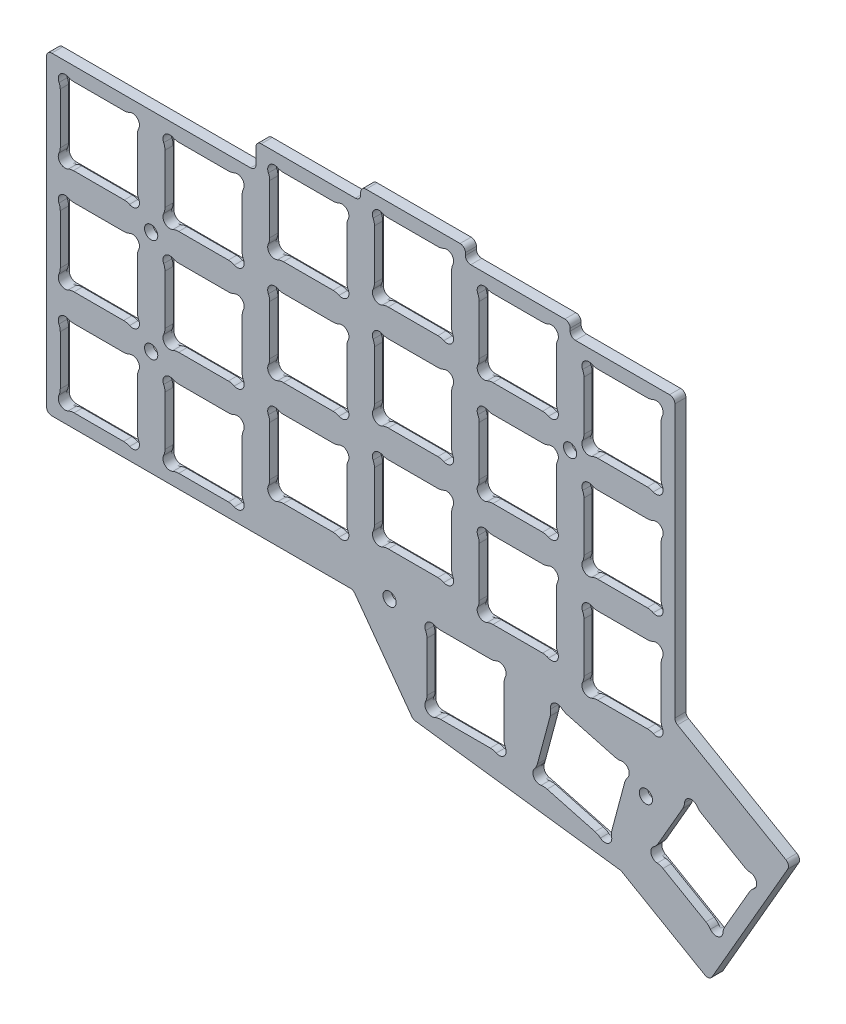
SolidWorks part; units mm, degrees
ref_plane "Front Plane" through (0, 0, 0) normal (0, 0, 1) x (1, 0, 0)
ref_plane "Top Plane" through (0, 0, 0) normal (0, 1, 0) x (1, 0, 0)
ref_plane "Right Plane" through (0, 0, 0) normal (1, 0, 0) x (0, 0, -1)
sketch "Model" plane through (0, 0, 0) normal (0, 0, 1) x (1, 0, 0)
  line L0 (-21.8431, 7.4481) -> (-8.6148, 30.3792)
  line L1 (-38.0636, 15.3297) -> (-23.771, 7.0696)
  line L2 (-75.3888, 20.2293) -> (-38.7189, 15.4592)
  line L3 (-86.2854, 34.8343) -> (-75.7419, 20.3766)
  line L4 (-29.1405, 92.9799) -> (-29.1405, 91.7303)
  line L5 (-8.8891, 91.2299) -> (-28.6402, 91.2299)
  line L6 (-8.3888, 90.7295) -> (-8.3888, 31.2555)
  line L7 (-86.6385, 34.9791) -> (-141.6396, 34.9791)
  line L8 (-142.1399, 90.7295) -> (-142.1399, 35.4795)
  line L9 (-104.6394, 91.2299) -> (-141.6396, 91.2299)
  line L10 (-104.139, 95.4793) -> (-104.139, 91.7303)
  line L11 (-85.6402, 95.9797) -> (-103.6387, 95.9797)
  line L12 (-85.1399, 97.7297) -> (-85.1399, 96.4801)
  line L13 (-67.6393, 98.2301) -> (-84.6395, 98.2301)
  line L14 (-67.1389, 96.4801) -> (-67.1389, 97.7297)
  line L15 (-48.6401, 95.9797) -> (-66.6385, 95.9797)
  line L16 (-48.1397, 93.9807) -> (-48.1397, 95.4793)
  line L17 (-29.6384, 93.4803) -> (-47.6393, 93.4803)
  line L18 (135.1563, 30.6526) -> (116.2359, 41.5721)
  line L19 (123.1828, 7.2669) -> (135.5373, 28.7222)
  line L20 (106.9623, 15.1485) -> (121.2549, 6.8884)
  line L21 (69.6371, 20.0481) -> (106.307, 15.278)
  line L22 (58.7405, 34.6531) -> (69.284, 20.1955)
  line L23 (115.8854, 92.7987) -> (115.8828, 42.2376)
  line L24 (58.3874, 34.7979) -> (3.3863, 34.7979)
  line L25 (2.886, 90.5483) -> (2.886, 35.2983)
  line L26 (40.3865, 91.0487) -> (3.3863, 91.0487)
  line L27 (40.8869, 95.2981) -> (40.8869, 91.5491)
  line L28 (59.3857, 95.7985) -> (41.3872, 95.7985)
  line L29 (59.886, 97.5485) -> (59.886, 96.2989)
  line L30 (77.3866, 98.0489) -> (60.3864, 98.0489)
  line L31 (77.887, 96.2989) -> (77.887, 97.5485)
  line L32 (96.3858, 95.7985) -> (78.3874, 95.7985)
  line L33 (96.8862, 93.7995) -> (96.8862, 95.2981)
  line L34 (115.3875, 93.2991) -> (97.3866, 93.2991)
  line L35 (20.1915, -96.2476) -> (6.9631, -73.3165)
  line L36 (36.4119, -88.366) -> (22.1193, -96.6261)
  line L37 (73.7371, -83.4663) -> (37.0672, -88.2365)
  line L38 (84.6337, -68.8614) -> (74.0902, -83.319)
  line L39 (27.4889, -10.7157) -> (27.4889, -11.9654)
  line L40 (7.2375, -12.4658) -> (26.9885, -12.4658)
  line L41 (6.7371, -12.9662) -> (6.7371, -72.4402)
  line L42 (84.9868, -68.7166) -> (139.9879, -68.7166)
  line L43 (140.4883, -12.9662) -> (140.4883, -68.2162)
  line L44 (102.9878, -12.4658) -> (139.9879, -12.4658)
  line L45 (102.4874, -8.2164) -> (102.4874, -11.9654)
  line L46 (83.9886, -7.716) -> (101.987, -7.716)
  line L47 (83.4882, -5.9659) -> (83.4882, -7.2156)
  line L48 (65.9876, -5.4656) -> (82.9878, -5.4656)
  line L49 (65.4872, -7.2156) -> (65.4872, -5.9659)
  line L50 (46.9884, -7.716) -> (64.9869, -7.716)
  line L51 (46.488, -9.715) -> (46.488, -8.2164)
  line L52 (27.9867, -10.2154) -> (45.9877, -10.2154)
  line L53 (-136.808, -73.043) -> (-117.8876, -62.1236)
  line L54 (-124.8344, -96.4288) -> (-137.189, -74.9734)
  line L55 (-108.614, -88.5472) -> (-122.9066, -96.8073)
  line L56 (-71.2888, -83.6475) -> (-107.9587, -88.4176)
  line L57 (-60.3922, -69.0425) -> (-70.9357, -83.5002)
  line L58 (-117.537, -10.8969) -> (-117.5345, -61.4581)
  line L59 (-60.0391, -68.8978) -> (-5.038, -68.8978)
  line L60 (-4.5376, -13.1474) -> (-4.5376, -68.3974)
  line L61 (-42.0381, -12.647) -> (-5.038, -12.647)
  line L62 (-42.5385, -8.3976) -> (-42.5385, -12.1466)
  line L63 (-61.0373, -7.8972) -> (-43.0389, -7.8972)
  line L64 (-61.5377, -6.1471) -> (-61.5377, -7.3968)
  line L65 (-79.0383, -5.6467) -> (-62.0381, -5.6467)
  line L66 (-79.5387, -7.3968) -> (-79.5387, -6.1471)
  line L67 (-98.0375, -7.8972) -> (-80.039, -7.8972)
  line L68 (-98.5378, -9.8962) -> (-98.5378, -8.3976)
  line L69 (-117.0392, -10.3965) -> (-99.0382, -10.3965)
  line L70 (138.9148, 92.1117) -> (138.9148, 33.3582)
  line L71 (138.1649, 32.9251) -> (119.446, 43.7282)
  line L72 (119.196, 44.1613) -> (119.196, 92.1092)
  line L73 (119.6959, 92.6092) -> (138.4148, 92.6117)
  line L74 (-140.5665, -11.584) -> (-140.5665, -70.3375)
  line L75 (-139.8166, -70.7706) -> (-121.0977, -59.9674)
  line L76 (-120.8476, -59.5344) -> (-120.8476, -11.5865)
  line L77 (-121.3476, -11.0865) -> (-140.0664, -11.084)
  line L78 (18.8966, 74.9256) -> (4.8966, 74.9256)
  line L79 (4.8966, 74.9256) -> (4.8966, 88.9256)
  line L80 (4.8966, 88.9256) -> (18.8966, 88.9256)
  line L81 (18.8966, 88.9256) -> (18.8966, 74.9256)
  line L82 (18.8966, 55.9256) -> (4.8966, 55.9256)
  line L83 (4.8966, 55.9256) -> (4.8966, 69.9256)
  line L84 (4.8966, 69.9256) -> (18.8966, 69.9256)
  line L85 (18.8966, 69.9256) -> (18.8966, 55.9256)
  line L86 (18.8966, 36.9256) -> (4.8966, 36.9256)
  line L87 (4.8966, 36.9256) -> (4.8966, 50.9256)
  line L88 (4.8966, 50.9256) -> (18.8966, 50.9256)
  line L89 (18.8966, 50.9256) -> (18.8966, 36.9256)
  line L90 (37.8948, 74.9262) -> (23.8948, 74.9262)
  line L91 (23.8948, 74.9262) -> (23.8948, 88.9262)
  line L92 (23.8948, 88.9262) -> (37.8948, 88.9262)
  line L93 (37.8948, 88.9262) -> (37.8948, 74.9262)
  line L94 (37.8948, 55.9262) -> (23.8948, 55.9262)
  line L95 (23.8948, 55.9262) -> (23.8948, 69.9262)
  line L96 (23.8948, 69.9262) -> (37.8948, 69.9262)
  line L97 (37.8948, 69.9262) -> (37.8948, 55.9262)
  line L98 (37.8948, 36.9262) -> (23.8948, 36.9262)
  line L99 (23.8948, 36.9262) -> (23.8948, 50.9262)
  line L100 (23.8948, 50.9262) -> (37.8948, 50.9262)
  line L101 (37.8948, 50.9262) -> (37.8948, 36.9262)
  line L102 (56.895, 79.671) -> (42.895, 79.671)
  line L103 (42.895, 79.671) -> (42.895, 93.671)
  line L104 (42.895, 93.671) -> (56.895, 93.671)
  line L105 (56.895, 93.671) -> (56.895, 79.671)
  line L106 (56.895, 60.6711) -> (42.895, 60.6711)
  line L107 (42.895, 60.6711) -> (42.895, 74.6711)
  line L108 (42.895, 74.6711) -> (56.895, 74.6711)
  line L109 (56.895, 74.6711) -> (56.895, 60.6711)
  line L110 (56.895, 41.6711) -> (42.895, 41.6711)
  line L111 (42.895, 41.6711) -> (42.895, 55.6711)
  line L112 (42.895, 55.6711) -> (56.895, 55.6711)
  line L113 (56.895, 55.6711) -> (56.895, 41.6711)
  line L114 (75.897, 82.0499) -> (61.897, 82.0499)
  line L115 (61.897, 82.0499) -> (61.897, 96.0499)
  line L116 (61.897, 96.0499) -> (75.897, 96.0499)
  line L117 (75.897, 96.0499) -> (75.897, 82.0499)
  line L118 (75.897, 63.0499) -> (61.897, 63.0499)
  line L119 (61.897, 63.0499) -> (61.897, 77.0499)
  line L120 (61.897, 77.0499) -> (75.897, 77.0499)
  line L121 (75.897, 77.0499) -> (75.897, 63.0499)
  line L122 (75.897, 44.0499) -> (61.897, 44.0499)
  line L123 (61.897, 44.0499) -> (61.897, 58.0499)
  line L124 (61.897, 58.0499) -> (75.897, 58.0499)
  line L125 (75.897, 58.0499) -> (75.897, 44.0499)
  line L126 (94.8982, 79.6753) -> (80.8982, 79.6753)
  line L127 (80.8982, 79.6753) -> (80.8982, 93.6753)
  line L128 (80.8982, 93.6753) -> (94.8982, 93.6753)
  line L129 (94.8982, 93.6753) -> (94.8982, 79.6753)
  line L130 (94.8982, 60.6753) -> (80.8982, 60.6753)
  line L131 (80.8982, 60.6753) -> (80.8982, 74.6753)
  line L132 (80.8982, 74.6753) -> (94.8982, 74.6753)
  line L133 (94.8982, 74.6753) -> (94.8982, 60.6753)
  line L134 (94.8982, 41.6753) -> (80.8982, 41.6753)
  line L135 (80.8982, 41.6753) -> (80.8982, 55.6753)
  line L136 (80.8982, 55.6753) -> (94.8982, 55.6753)
  line L137 (94.8982, 55.6753) -> (94.8982, 41.6753)
  line L138 (113.9, 77.2905) -> (99.9, 77.2905)
  line L139 (99.9, 77.2905) -> (99.9, 91.2905)
  line L140 (99.9, 91.2905) -> (113.9, 91.2905)
  line L141 (113.9, 91.2905) -> (113.9, 77.2905)
  line L142 (113.9, 58.2905) -> (99.9, 58.2905)
  line L143 (99.9, 58.2905) -> (99.9, 72.2905)
  line L144 (99.9, 72.2905) -> (113.9, 72.2905)
  line L145 (113.9, 72.2905) -> (113.9, 58.2905)
  line L146 (113.9, 39.2905) -> (99.9, 39.2905)
  line L147 (99.9, 39.2905) -> (99.9, 53.2905)
  line L148 (99.9, 53.2905) -> (113.9, 53.2905)
  line L149 (113.9, 53.2905) -> (113.9, 39.2905)
  line L150 (85.4166, 22.0174) -> (71.4166, 22.0174)
  line L151 (71.4166, 22.0174) -> (71.4166, 36.0174)
  line L152 (71.4166, 36.0174) -> (85.4166, 36.0174)
  line L153 (85.4166, 36.0174) -> (85.4166, 22.0174)
  line L154 (104.3289, 17.734) -> (90.806, 21.3575)
  line L155 (90.806, 21.3575) -> (94.4294, 34.8805)
  line L156 (94.4294, 34.8805) -> (107.9524, 31.257)
  line L157 (107.9524, 31.257) -> (104.3289, 17.734)
  line L158 (124.1994, 13.0049) -> (112.075, 20.0049)
  line L159 (112.075, 20.0049) -> (119.075, 32.1293)
  line L160 (119.075, 32.1293) -> (131.1994, 25.1293)
  line L161 (131.1994, 25.1293) -> (124.1994, 13.0049)
  line L162 (-20.5483, -28.7701) -> (-6.5483, -28.7701)
  line L163 (-6.5483, -28.7701) -> (-6.5483, -14.7701)
  line L164 (-6.5483, -14.7701) -> (-20.5483, -14.7701)
  line L165 (-20.5483, -14.7701) -> (-20.5483, -28.7701)
  line L166 (-20.5483, -47.7701) -> (-6.5483, -47.7701)
  line L167 (-6.5483, -47.7701) -> (-6.5483, -33.7701)
  line L168 (-6.5483, -33.7701) -> (-20.5483, -33.7701)
  line L169 (-20.5483, -33.7701) -> (-20.5483, -47.7701)
  line L170 (-20.5483, -66.7701) -> (-6.5483, -66.7701)
  line L171 (-6.5483, -66.7701) -> (-6.5483, -52.7701)
  line L172 (-6.5483, -52.7701) -> (-20.5483, -52.7701)
  line L173 (-20.5483, -52.7701) -> (-20.5483, -66.7701)
  line L174 (-39.5464, -28.7694) -> (-25.5464, -28.7694)
  line L175 (-25.5464, -28.7694) -> (-25.5464, -14.7694)
  line L176 (-25.5464, -14.7694) -> (-39.5464, -14.7694)
  line L177 (-39.5464, -14.7694) -> (-39.5464, -28.7694)
  line L178 (-39.5464, -47.7694) -> (-25.5464, -47.7694)
  line L179 (-25.5464, -47.7694) -> (-25.5464, -33.7694)
  line L180 (-25.5464, -33.7694) -> (-39.5464, -33.7694)
  line L181 (-39.5464, -33.7694) -> (-39.5464, -47.7694)
  line L182 (-39.5464, -66.7694) -> (-25.5464, -66.7694)
  line L183 (-25.5464, -66.7694) -> (-25.5464, -52.7694)
  line L184 (-25.5464, -52.7694) -> (-39.5464, -52.7694)
  line L185 (-39.5464, -52.7694) -> (-39.5464, -66.7694)
  line L186 (-58.5467, -24.0246) -> (-44.5467, -24.0246)
  line L187 (-44.5467, -24.0246) -> (-44.5467, -10.0246)
  line L188 (-44.5467, -10.0246) -> (-58.5467, -10.0246)
  line L189 (-58.5467, -10.0246) -> (-58.5467, -24.0246)
  line L190 (-58.5467, -43.0246) -> (-44.5467, -43.0246)
  line L191 (-44.5467, -43.0246) -> (-44.5467, -29.0246)
  line L192 (-44.5467, -29.0246) -> (-58.5467, -29.0246)
  line L193 (-58.5467, -29.0246) -> (-58.5467, -43.0246)
  line L194 (-58.5467, -62.0246) -> (-44.5467, -62.0246)
  line L195 (-44.5467, -62.0246) -> (-44.5467, -48.0246)
  line L196 (-44.5467, -48.0246) -> (-58.5467, -48.0246)
  line L197 (-58.5467, -48.0246) -> (-58.5467, -62.0246)
  line L198 (-77.5486, -21.6458) -> (-63.5486, -21.6458)
  line L199 (-63.5486, -21.6458) -> (-63.5486, -7.6458)
  line L200 (-63.5486, -7.6458) -> (-77.5486, -7.6458)
  line L201 (-77.5486, -7.6458) -> (-77.5486, -21.6458)
  line L202 (-77.5486, -40.6458) -> (-63.5486, -40.6458)
  line L203 (-63.5486, -40.6458) -> (-63.5486, -26.6458)
  line L204 (-63.5486, -26.6458) -> (-77.5486, -26.6458)
  line L205 (-77.5486, -26.6458) -> (-77.5486, -40.6458)
  line L206 (-77.5486, -59.6458) -> (-63.5486, -59.6458)
  line L207 (-63.5486, -59.6458) -> (-63.5486, -45.6458)
  line L208 (-63.5486, -45.6458) -> (-77.5486, -45.6458)
  line L209 (-77.5486, -45.6458) -> (-77.5486, -59.6458)
  line L210 (-96.5499, -24.0204) -> (-82.5499, -24.0204)
  line L211 (-82.5499, -24.0204) -> (-82.5499, -10.0204)
  line L212 (-82.5499, -10.0204) -> (-96.5499, -10.0204)
  line L213 (-96.5499, -10.0204) -> (-96.5499, -24.0204)
  line L214 (-96.5499, -43.0203) -> (-82.5499, -43.0203)
  line L215 (-82.5499, -43.0203) -> (-82.5499, -29.0203)
  line L216 (-82.5499, -29.0203) -> (-96.5499, -29.0203)
  line L217 (-96.5499, -29.0203) -> (-96.5499, -43.0203)
  line L218 (-96.5499, -62.0203) -> (-82.5499, -62.0203)
  line L219 (-82.5499, -62.0203) -> (-82.5499, -48.0203)
  line L220 (-82.5499, -48.0203) -> (-96.5499, -48.0203)
  line L221 (-96.5499, -48.0203) -> (-96.5499, -62.0203)
  line L222 (-115.5516, -26.4052) -> (-101.5516, -26.4052)
  line L223 (-101.5516, -26.4052) -> (-101.5516, -12.4052)
  line L224 (-101.5516, -12.4052) -> (-115.5516, -12.4052)
  line L225 (-115.5516, -12.4052) -> (-115.5516, -26.4052)
  line L226 (-115.5516, -45.4052) -> (-101.5516, -45.4052)
  line L227 (-101.5516, -45.4052) -> (-101.5516, -31.4052)
  line L228 (-101.5516, -31.4052) -> (-115.5516, -31.4052)
  line L229 (-115.5516, -31.4052) -> (-115.5516, -45.4052)
  line L230 (-115.5516, -64.4052) -> (-101.5516, -64.4052)
  line L231 (-101.5516, -64.4052) -> (-101.5516, -50.4052)
  line L232 (-101.5516, -50.4052) -> (-115.5516, -50.4052)
  line L233 (-115.5516, -50.4052) -> (-115.5516, -64.4052)
  line L234 (-87.0683, -81.6783) -> (-73.0683, -81.6783)
  line L235 (-73.0683, -81.6783) -> (-73.0683, -67.6783)
  line L236 (-73.0683, -67.6783) -> (-87.0683, -67.6783)
  line L237 (-87.0683, -67.6783) -> (-87.0683, -81.6783)
  line L238 (-105.9806, -85.9616) -> (-92.4576, -82.3382)
  line L239 (-92.4576, -82.3382) -> (-96.0811, -68.8152)
  line L240 (-96.0811, -68.8152) -> (-109.6041, -72.4387)
  line L241 (-109.6041, -72.4387) -> (-105.9806, -85.9616)
  line L242 (-125.851, -90.6908) -> (-113.7267, -83.6908)
  line L243 (-113.7267, -83.6908) -> (-120.7267, -71.5664)
  line L244 (-120.7267, -71.5664) -> (-132.851, -78.5664)
  line L245 (-132.851, -78.5664) -> (-125.851, -90.6908)
  spline S0 degree 3 poles (-8.6153, 30.3807) (-8.4626, 30.6458) (-8.3842, 30.9472) (-8.3882, 31.2532) knots 0 0 0 0 1 1 1 1
  spline S1 degree 3 poles (-21.8439, 7.4422) (-21.8429, 7.4437) (-21.8419, 7.4453) (-21.8408, 7.4468) knots 1 1 1 1 2 2 2 2
  spline S2 degree 3 poles (-23.769, 7.0673) (-23.1339, 6.6392) (-22.272, 6.8071) (-21.8439, 7.4422) knots 0 0 0 0 1 1 1 1
  spline S3 degree 3 poles (-38.063, 15.3284) (-38.2765, 15.3928) (-38.4957, 15.4362) (-38.7176, 15.4579) knots 0 0 0 0 1 1 1 1
  spline S4 degree 3 poles (-75.7416, 20.3746) (-75.6478, 20.2809) (-75.5206, 20.2283) (-75.3881, 20.2283) knots 0 0 0 0 1 1 1 1
  spline S5 degree 3 poles (-29.1383, 92.9782) (-29.1382, 93.2543) (-29.362, 93.4782) (-29.6381, 93.4783) knots 0 0 0 0 1 1 1 1
  spline S6 degree 3 poles (-29.1383, 91.7282) (-29.1383, 91.4521) (-28.9145, 91.2282) (-28.6384, 91.2281) (-28.6383, 91.2281) (-28.6382, 91.2281) (-28.6381, 91.2281) knots 0 0 0 0 1 1 1 2 2 2 2
  spline S7 degree 3 poles (-86.2846, 34.8318) (-86.3784, 34.9256) (-86.5056, 34.9783) (-86.6385, 34.9791) knots 0 0 0 0 1 1 1 1
  spline S8 degree 3 poles (-142.1382, 35.4782) (-142.1381, 35.2021) (-141.9142, 34.9783) (-141.6381, 34.9783) knots 0 0 0 0 1 1 1 1
  spline S9 degree 3 poles (-141.638, 91.2281) (-141.9142, 91.2282) (-142.1381, 91.0044) (-142.1382, 90.7282) knots 0 0 0 0 1 1 1 1
  spline S10 degree 3 poles (-104.6382, 91.2281) (-104.362, 91.228) (-104.1381, 91.4518) (-104.138, 91.728) (-104.138, 91.7281) (-104.138, 91.7281) (-104.138, 91.7282) knots 0 0 0 0 1 1 1 2 2 2 2
  spline S11 degree 3 poles (-103.6382, 95.9781) (-103.9142, 95.9781) (-104.138, 95.7543) (-104.138, 95.4783) knots 0 0 0 0 1 1 1 1
  spline S12 degree 3 poles (-85.6382, 95.9781) (-85.3621, 95.9781) (-85.1382, 96.2019) (-85.1381, 96.478) (-85.1381, 96.4781) (-85.1381, 96.4782) (-85.1381, 96.4783) knots 0 0 0 0 1 1 1 2 2 2 2
  spline S13 degree 3 poles (-84.6382, 98.2283) (-84.9144, 98.2283) (-85.1382, 98.0044) (-85.1381, 97.7282) knots 0 0 0 0 1 1 1 1
  spline S14 degree 3 poles (-67.1381, 97.7282) (-67.1381, 98.0043) (-67.3619, 98.2283) (-67.638, 98.2283) knots 0 0 0 0 2 2 2 2
  spline S15 degree 3 poles (-67.1381, 96.4783) (-67.1382, 96.2021) (-66.9144, 95.9782) (-66.6383, 95.9781) (-66.6382, 95.9781) (-66.6381, 95.9781) (-66.638, 95.9781) knots 0 0 0 0 1 1 1 2 2 2 2
  spline S16 degree 3 poles (-48.1382, 95.4783) (-48.1383, 95.7543) (-48.362, 95.9781) (-48.6381, 95.9781) knots 0 0 0 0 1 1 1 1
  spline S17 degree 3 poles (-48.1382, 93.9782) (-48.1381, 93.702) (-47.9142, 93.4782) (-47.6381, 93.4783) knots 0 0 0 0 1 1 1 1
  spline S18 degree 3 poles (-8.3882, 90.7282) (-8.3883, 91.0043) (-8.6121, 91.228) (-8.8881, 91.2281) knots 0 0 0 0 1 1 1 1
  spline S19 degree 3 poles (115.8851, 42.2368) (115.8929, 41.9725) (116.0232, 41.7268) (116.2377, 41.5721) knots 0 0 0 0 1 1 1 1
  spline S20 degree 3 poles (135.163, 30.647) (135.1614, 30.648) (135.1599, 30.6491) (135.1583, 30.6501) knots 1 1 1 1 2 2 2 2
  spline S21 degree 3 poles (135.5373, 28.7222) (135.9659, 29.3571) (135.7981, 30.2189) (135.163, 30.647) knots 0 0 0 0 1 1 1 1
  spline S22 degree 3 poles (123.182, 7.261) (123.183, 7.2625) (123.184, 7.2641) (123.1851, 7.2656) knots 1 1 1 1 2 2 2 2
  spline S23 degree 3 poles (121.2569, 6.8861) (121.892, 6.4581) (122.7539, 6.6259) (123.182, 7.261) knots 0 0 0 0 1 1 1 1
  spline S24 degree 3 poles (106.9629, 15.1472) (106.7494, 15.2117) (106.5302, 15.255) (106.3083, 15.2768) knots 0 0 0 0 1 1 1 1
  spline S25 degree 3 poles (69.2843, 20.1934) (69.3781, 20.0997) (69.5053, 20.0471) (69.6378, 20.0471) knots 0 0 0 0 1 1 1 1
  spline S26 degree 3 poles (115.8876, 92.797) (115.8877, 93.0731) (115.6639, 93.297) (115.3878, 93.2971) knots 0 0 0 0 1 1 1 1
  spline S27 degree 3 poles (58.7413, 34.6506) (58.6475, 34.7444) (58.5203, 34.7971) (58.3874, 34.7979) knots 0 0 0 0 1 1 1 1
  spline S28 degree 3 poles (2.8877, 35.297) (2.8878, 35.0209) (3.1117, 34.7971) (3.3878, 34.7971) knots 0 0 0 0 1 1 1 1
  spline S29 degree 3 poles (3.3879, 91.0469) (3.1117, 91.047) (2.8878, 90.8232) (2.8877, 90.547) knots 0 0 0 0 1 1 1 1
  spline S30 degree 3 poles (40.3877, 91.0469) (40.6639, 91.0468) (40.8878, 91.2706) (40.8879, 91.5468) (40.8879, 91.5469) (40.8879, 91.5469) (40.8879, 91.547) knots 0 0 0 0 1 1 1 2 2 2 2
  spline S31 degree 3 poles (41.3877, 95.797) (41.1117, 95.7969) (40.8879, 95.5731) (40.8879, 95.2971) knots 0 0 0 0 1 1 1 1
  spline S32 degree 3 poles (59.3877, 95.797) (59.6638, 95.7969) (59.8877, 96.0207) (59.8878, 96.2968) (59.8878, 96.2969) (59.8878, 96.297) (59.8878, 96.2971) knots 0 0 0 0 1 1 1 2 2 2 2
  spline S33 degree 3 poles (60.3877, 98.0471) (60.1115, 98.0471) (59.8877, 97.8232) (59.8878, 97.547) knots 0 0 0 0 1 1 1 1
  spline S34 degree 3 poles (77.8878, 97.547) (77.8878, 97.8232) (77.664, 98.0471) (77.3879, 98.0471) knots 0 0 0 0 2 2 2 2
  spline S35 degree 3 poles (77.8878, 96.2971) (77.8877, 96.0209) (78.1115, 95.797) (78.3876, 95.797) (78.3877, 95.797) (78.3878, 95.797) (78.3879, 95.797) knots 0 0 0 0 1 1 1 2 2 2 2
  spline S36 degree 3 poles (96.8877, 95.2971) (96.8876, 95.5731) (96.6639, 95.7969) (96.3878, 95.797) knots 0 0 0 0 1 1 1 1
  spline S37 degree 3 poles (96.8877, 93.797) (96.8878, 93.5208) (97.1117, 93.297) (97.3878, 93.2971) knots 0 0 0 0 1 1 1 1
  spline S38 degree 3 poles (6.9637, -73.315) (6.8109, -73.0499) (6.7325, -72.7484) (6.7366, -72.4425) knots 0 0 0 0 1 1 1 1
  spline S39 degree 3 poles (20.1923, -96.2535) (20.1912, -96.252) (20.1902, -96.2504) (20.1892, -96.2489) knots 1 1 1 1 2 2 2 2
  spline S40 degree 3 poles (22.1173, -96.6284) (21.4822, -97.0564) (20.6203, -96.8886) (20.1923, -96.2535) knots 0 0 0 0 1 1 1 1
  spline S41 degree 3 poles (36.4114, -88.3673) (36.6248, -88.3028) (36.844, -88.2594) (37.0659, -88.2377) knots 0 0 0 0 1 1 1 1
  spline S42 degree 3 poles (74.0899, -83.3211) (73.9962, -83.4148) (73.869, -83.4674) (73.7364, -83.4674) knots 0 0 0 0 1 1 1 1
  spline S43 degree 3 poles (27.4866, -10.7175) (27.4865, -10.4414) (27.7103, -10.2175) (27.9865, -10.2174) knots 0 0 0 0 1 1 1 1
  spline S44 degree 3 poles (27.4866, -11.9674) (27.4866, -12.2436) (27.2628, -12.4675) (26.9867, -12.4676) (26.9866, -12.4676) (26.9865, -12.4676) (26.9865, -12.4676) knots 0 0 0 0 1 1 1 2 2 2 2
  spline S45 degree 3 poles (84.633, -68.8639) (84.7267, -68.7701) (84.8539, -68.7174) (84.9868, -68.7166) knots 0 0 0 0 1 1 1 1
  spline S46 degree 3 poles (140.4865, -68.2175) (140.4864, -68.4936) (140.2625, -68.7174) (139.9864, -68.7173) knots 0 0 0 0 1 1 1 1
  spline S47 degree 3 poles (139.9864, -12.4676) (140.2625, -12.4675) (140.4864, -12.6913) (140.4865, -12.9674) knots 0 0 0 0 1 1 1 1
  spline S48 degree 3 poles (102.9865, -12.4676) (102.7103, -12.4676) (102.4864, -12.2438) (102.4864, -11.9677) (102.4864, -11.9676) (102.4864, -11.9675) (102.4864, -11.9674) knots 0 0 0 0 1 1 1 2 2 2 2
  spline S49 degree 3 poles (101.9865, -7.7175) (102.2625, -7.7176) (102.4863, -7.9413) (102.4864, -8.2174) knots 0 0 0 0 1 1 1 1
  spline S50 degree 3 poles (83.9865, -7.7175) (83.7104, -7.7176) (83.4865, -7.4938) (83.4864, -7.2176) (83.4864, -7.2176) (83.4864, -7.2175) (83.4864, -7.2174) knots 0 0 0 0 1 1 1 2 2 2 2
  spline S51 degree 3 poles (82.9865, -5.4673) (83.2627, -5.4674) (83.4865, -5.6913) (83.4864, -5.9675) knots 0 0 0 0 1 1 1 1
  spline S52 degree 3 poles (65.4865, -5.9675) (65.4864, -5.6913) (65.7102, -5.4674) (65.9863, -5.4673) knots 0 0 0 0 2 2 2 2
  spline S53 degree 3 poles (65.4865, -7.2174) (65.4865, -7.4935) (65.2627, -7.7174) (64.9866, -7.7175) (64.9865, -7.7175) (64.9864, -7.7175) (64.9863, -7.7175) knots 0 0 0 0 1 1 1 2 2 2 2
  spline S54 degree 3 poles (46.4865, -8.2174) (46.4866, -7.9413) (46.7103, -7.7176) (46.9864, -7.7175) knots 0 0 0 0 1 1 1 1
  spline S55 degree 3 poles (46.4865, -9.7175) (46.4865, -9.9937) (46.2625, -10.2175) (45.9864, -10.2174) knots 0 0 0 0 1 1 1 1
  spline S56 degree 3 poles (6.7366, -12.9674) (6.7366, -12.6914) (6.9604, -12.4676) (7.2365, -12.4676) knots 0 0 0 0 1 1 1 1
  spline S57 degree 3 poles (-117.5368, -61.4589) (-117.5446, -61.7232) (-117.6748, -61.9689) (-117.8893, -62.1236) knots 0 0 0 0 1 1 1 1
  spline S58 degree 3 poles (-136.8146, -73.0487) (-136.8131, -73.0476) (-136.8116, -73.0466) (-136.81, -73.0456) knots 1 1 1 1 2 2 2 2
  spline S59 degree 3 poles (-137.189, -74.9734) (-137.6176, -74.3386) (-137.4497, -73.4767) (-136.8146, -73.0487) knots 0 0 0 0 1 1 1 1
  spline S60 degree 3 poles (-124.8336, -96.4347) (-124.8347, -96.4331) (-124.8357, -96.4316) (-124.8367, -96.4301) knots 1 1 1 1 2 2 2 2
  spline S61 degree 3 poles (-122.9086, -96.8095) (-123.5437, -97.2376) (-124.4056, -97.0698) (-124.8336, -96.4347) knots 0 0 0 0 1 1 1 1
  spline S62 degree 3 poles (-108.6145, -88.5485) (-108.4011, -88.484) (-108.1819, -88.4406) (-107.96, -88.4189) knots 0 0 0 0 1 1 1 1
  spline S63 degree 3 poles (-70.936, -83.5022) (-71.0297, -83.596) (-71.1569, -83.6486) (-71.2895, -83.6485) knots 0 0 0 0 1 1 1 1
  spline S64 degree 3 poles (-117.5393, -10.8987) (-117.5394, -10.6226) (-117.3156, -10.3987) (-117.0394, -10.3986) knots 0 0 0 0 1 1 1 1
  spline S65 degree 3 poles (-60.3929, -69.0451) (-60.2992, -68.9513) (-60.172, -68.8986) (-60.0391, -68.8978) knots 0 0 0 0 1 1 1 1
  spline S66 degree 3 poles (-4.5394, -68.3987) (-4.5395, -68.6748) (-4.7634, -68.8986) (-5.0395, -68.8985) knots 0 0 0 0 1 1 1 1
  spline S67 degree 3 poles (-5.0395, -12.6488) (-4.7634, -12.6487) (-4.5395, -12.8725) (-4.5394, -13.1486) knots 0 0 0 0 1 1 1 1
  spline S68 degree 3 poles (-42.0394, -12.6488) (-42.3156, -12.6488) (-42.5395, -12.425) (-42.5395, -12.1489) (-42.5395, -12.1488) (-42.5395, -12.1487) (-42.5395, -12.1486) knots 0 0 0 0 1 1 1 2 2 2 2
  spline S69 degree 3 poles (-43.0394, -7.8987) (-42.7634, -7.8988) (-42.5396, -8.1225) (-42.5395, -8.3986) knots 0 0 0 0 1 1 1 1
  spline S70 degree 3 poles (-61.0394, -7.8987) (-61.3155, -7.8988) (-61.5394, -7.675) (-61.5395, -7.3988) (-61.5395, -7.3988) (-61.5395, -7.3987) (-61.5395, -7.3986) knots 0 0 0 0 1 1 1 2 2 2 2
  spline S71 degree 3 poles (-62.0394, -5.6485) (-61.7632, -5.6486) (-61.5394, -5.8725) (-61.5395, -6.1486) knots 0 0 0 0 1 1 1 1
  spline S72 degree 3 poles (-79.5394, -6.1486) (-79.5395, -5.8725) (-79.3157, -5.6486) (-79.0396, -5.6485) knots 0 0 0 0 2 2 2 2
  spline S73 degree 3 poles (-79.5394, -7.3986) (-79.5394, -7.6747) (-79.7632, -7.8986) (-80.0393, -7.8987) (-80.0394, -7.8987) (-80.0395, -7.8987) (-80.0396, -7.8987) knots 0 0 0 0 1 1 1 2 2 2 2
  spline S74 degree 3 poles (-98.5394, -8.3986) (-98.5393, -8.1225) (-98.3156, -7.8988) (-98.0395, -7.8987) knots 0 0 0 0 1 1 1 1
  spline S75 degree 3 poles (-98.5394, -9.8987) (-98.5394, -10.1748) (-98.7634, -10.3986) (-99.0395, -10.3986) knots 0 0 0 0 1 1 1 1
  spline S76 degree 3 poles (-123.6381, 52.6314) (-124.2456, 52.6314) (-124.7381, 53.1239) (-124.7381, 53.7314) (-124.7381, 54.3389) (-124.2456, 54.8314) (-123.6381, 54.8314) knots 2 2 2 2 3 3 3 4 4 4 4
  spline S77 degree 3 poles (-123.6381, 54.8314) (-123.0306, 54.8314) (-122.5381, 54.3389) (-122.5381, 53.7314) (-122.5381, 53.1239) (-123.0306, 52.6314) (-123.6381, 52.6314) knots 0 0 0 0 1 1 1 2 2 2 2
  spline S78 degree 3 poles (-123.6381, 71.3814) (-124.2456, 71.3814) (-124.7381, 71.8739) (-124.7381, 72.4814) (-124.7381, 73.0889) (-124.2456, 73.5814) (-123.6381, 73.5814) knots 2 2 2 2 3 3 3 4 4 4 4
  spline S79 degree 3 poles (-123.6381, 73.5814) (-123.0306, 73.5814) (-122.5381, 73.0889) (-122.5381, 72.4814) (-122.5381, 71.8739) (-123.0306, 71.3814) (-123.6381, 71.3814) knots 0 0 0 0 1 1 1 2 2 2 2
  spline S80 degree 3 poles (-47.6381, 75.1312) (-48.2456, 75.1312) (-48.7381, 75.6237) (-48.7381, 76.2312) (-48.7381, 76.8387) (-48.2456, 77.3312) (-47.6381, 77.3312) knots 2 2 2 2 3 3 3 4 4 4 4
  spline S81 degree 3 poles (-47.6381, 77.3312) (-47.0306, 77.3312) (-46.5381, 76.8387) (-46.5381, 76.2312) (-46.5381, 75.6237) (-47.0306, 75.1312) (-47.6381, 75.1312) knots 0 0 0 0 1 1 1 2 2 2 2
  spline S82 degree 3 poles (-80.388, 35.3813) (-80.9956, 35.3813) (-81.488, 35.8738) (-81.488, 36.4813) (-81.488, 37.0888) (-80.9956, 37.5813) (-80.388, 37.5813) knots 2 2 2 2 3 3 3 4 4 4 4
  spline S83 degree 3 poles (-80.388, 37.5813) (-79.7805, 37.5813) (-79.288, 37.0888) (-79.288, 36.4813) (-79.288, 35.8738) (-79.7805, 35.3813) (-80.388, 35.3813) knots 0 0 0 0 1 1 1 2 2 2 2
  spline S84 degree 3 poles (-33.8881, 27.6312) (-34.4956, 27.6312) (-34.9881, 28.1237) (-34.9881, 28.7312) (-34.9881, 29.3388) (-34.4956, 29.8312) (-33.8881, 29.8312) knots 2 2 2 2 3 3 3 4 4 4 4
  spline S85 degree 3 poles (-33.8881, 29.8312) (-33.2805, 29.8312) (-32.7881, 29.3388) (-32.7881, 28.7312) (-32.7881, 28.1237) (-33.2805, 27.6312) (-33.8881, 27.6312) knots 0 0 0 0 1 1 1 2 2 2 2
  spline S86 degree 3 poles (21.3878, 52.4502) (20.7803, 52.4502) (20.2878, 52.9427) (20.2878, 53.5502) (20.2878, 54.1578) (20.7803, 54.6502) (21.3878, 54.6502) knots 2 2 2 2 3 3 3 4 4 4 4
  spline S87 degree 3 poles (21.3878, 54.6502) (21.9953, 54.6502) (22.4878, 54.1578) (22.4878, 53.5502) (22.4878, 52.9427) (21.9953, 52.4502) (21.3878, 52.4502) knots 0 0 0 0 1 1 1 2 2 2 2
  spline S88 degree 3 poles (97.3878, 74.95) (96.7803, 74.95) (96.2878, 75.4425) (96.2878, 76.05) (96.2878, 76.6575) (96.7803, 77.15) (97.3878, 77.15) knots 2 2 2 2 3 3 3 4 4 4 4
  spline S89 degree 3 poles (97.3878, 77.15) (97.9953, 77.15) (98.4878, 76.6575) (98.4878, 76.05) (98.4878, 75.4425) (97.9953, 74.95) (97.3878, 74.95) knots 0 0 0 0 1 1 1 2 2 2 2
  spline S90 degree 3 poles (64.6379, 35.2001) (64.0303, 35.2001) (63.5379, 35.6926) (63.5379, 36.3001) (63.5379, 36.9076) (64.0303, 37.4001) (64.6379, 37.4001) knots 2 2 2 2 3 3 3 4 4 4 4
  spline S91 degree 3 poles (64.6379, 37.4001) (65.2454, 37.4001) (65.7379, 36.9076) (65.7379, 36.3001) (65.7379, 35.6926) (65.2454, 35.2001) (64.6379, 35.2001) knots 0 0 0 0 1 1 1 2 2 2 2
  spline S92 degree 3 poles (111.1378, 27.4501) (110.5303, 27.4501) (110.0378, 27.9425) (110.0378, 28.5501) (110.0378, 29.1576) (110.5303, 29.65) (111.1378, 29.65) knots 2 2 2 2 3 3 3 4 4 4 4
  spline S93 degree 3 poles (111.1378, 29.65) (111.7454, 29.65) (112.2378, 29.1576) (112.2378, 28.5501) (112.2378, 27.9425) (111.7454, 27.4501) (111.1378, 27.4501) knots 0 0 0 0 1 1 1 2 2 2 2
  spline S94 degree 3 poles (121.9864, -51.0642) (122.5939, -51.0642) (123.0864, -50.5718) (123.0864, -49.9642) (123.0864, -49.3567) (122.5939, -48.8642) (121.9864, -48.8642) knots 2 2 2 2 3 3 3 4 4 4 4
  spline S95 degree 3 poles (121.9864, -48.8642) (121.3789, -48.8642) (120.8864, -49.3567) (120.8864, -49.9642) (120.8864, -50.5718) (121.3789, -51.0642) (121.9864, -51.0642) knots 0 0 0 0 1 1 1 2 2 2 2
  spline S96 degree 3 poles (121.9864, -32.3142) (122.5939, -32.3142) (123.0864, -31.8218) (123.0864, -31.2142) (123.0864, -30.6067) (122.5939, -30.1142) (121.9864, -30.1142) knots 2 2 2 2 3 3 3 4 4 4 4
  spline S97 degree 3 poles (121.9864, -30.1142) (121.3789, -30.1142) (120.8864, -30.6067) (120.8864, -31.2142) (120.8864, -31.8218) (121.3789, -32.3142) (121.9864, -32.3142) knots 0 0 0 0 1 1 1 2 2 2 2
  spline S98 degree 3 poles (45.9864, -28.5644) (46.5939, -28.5644) (47.0864, -28.072) (47.0864, -27.4644) (47.0864, -26.8569) (46.5939, -26.3644) (45.9864, -26.3644) knots 2 2 2 2 3 3 3 4 4 4 4
  spline S99 degree 3 poles (45.9864, -26.3644) (45.3789, -26.3644) (44.8864, -26.8569) (44.8864, -27.4644) (44.8864, -28.072) (45.3789, -28.5644) (45.9864, -28.5644) knots 0 0 0 0 1 1 1 2 2 2 2
  spline S100 degree 3 poles (78.7364, -68.3144) (79.3439, -68.3144) (79.8364, -67.8219) (79.8364, -67.2144) (79.8364, -66.6069) (79.3439, -66.1144) (78.7364, -66.1144) knots 2 2 2 2 3 3 3 4 4 4 4
  spline S101 degree 3 poles (78.7364, -66.1144) (78.1288, -66.1144) (77.6364, -66.6069) (77.6364, -67.2144) (77.6364, -67.8219) (78.1288, -68.3144) (78.7364, -68.3144) knots 0 0 0 0 1 1 1 2 2 2 2
  spline S102 degree 3 poles (32.2364, -76.0644) (32.8439, -76.0644) (33.3364, -75.5719) (33.3364, -74.9644) (33.3364, -74.3569) (32.8439, -73.8644) (32.2364, -73.8644) knots 2 2 2 2 3 3 3 4 4 4 4
  spline S103 degree 3 poles (32.2364, -73.8644) (31.6289, -73.8644) (31.1364, -74.3569) (31.1364, -74.9644) (31.1364, -75.5719) (31.6289, -76.0644) (32.2364, -76.0644) knots 0 0 0 0 1 1 1 2 2 2 2
  spline S104 degree 3 poles (-23.0395, -51.2454) (-22.432, -51.2454) (-21.9395, -50.7529) (-21.9395, -50.1454) (-21.9395, -49.5379) (-22.432, -49.0454) (-23.0395, -49.0454) knots 2 2 2 2 3 3 3 4 4 4 4
  spline S105 degree 3 poles (-23.0395, -49.0454) (-23.647, -49.0454) (-24.1395, -49.5379) (-24.1395, -50.1454) (-24.1395, -50.7529) (-23.647, -51.2454) (-23.0395, -51.2454) knots 0 0 0 0 1 1 1 2 2 2 2
  spline S106 degree 3 poles (-99.0395, -28.7456) (-98.432, -28.7456) (-97.9395, -28.2531) (-97.9395, -27.6456) (-97.9395, -27.0381) (-98.432, -26.5456) (-99.0395, -26.5456) knots 2 2 2 2 3 3 3 4 4 4 4
  spline S107 degree 3 poles (-99.0395, -26.5456) (-99.647, -26.5456) (-100.1395, -27.0381) (-100.1395, -27.6456) (-100.1395, -28.2531) (-99.647, -28.7456) (-99.0395, -28.7456) knots 0 0 0 0 1 1 1 2 2 2 2
  spline S108 degree 3 poles (-66.2895, -68.4956) (-65.682, -68.4956) (-65.1895, -68.0031) (-65.1895, -67.3956) (-65.1895, -66.7881) (-65.682, -66.2956) (-66.2895, -66.2956) knots 2 2 2 2 3 3 3 4 4 4 4
  spline S109 degree 3 poles (-66.2895, -66.2956) (-66.8971, -66.2956) (-67.3895, -66.7881) (-67.3895, -67.3956) (-67.3895, -68.0031) (-66.8971, -68.4956) (-66.2895, -68.4956) knots 0 0 0 0 1 1 1 2 2 2 2
  spline S110 degree 3 poles (-112.7895, -76.2456) (-112.182, -76.2456) (-111.6895, -75.7531) (-111.6895, -75.1456) (-111.6895, -74.5381) (-112.182, -74.0456) (-112.7895, -74.0456) knots 2 2 2 2 3 3 3 4 4 4 4
  spline S111 degree 3 poles (-112.7895, -74.0456) (-113.397, -74.0456) (-113.8895, -74.5381) (-113.8895, -75.1456) (-113.8895, -75.7531) (-113.397, -76.2456) (-112.7895, -76.2456) knots 0 0 0 0 1 1 1 2 2 2 2
  spline S112 degree 3 poles (138.9148, 33.3582) (138.9148, 32.9733) (138.4982, 32.7327) (138.1649, 32.9251) knots 1 1 1 1 2 2 2 2
  spline S113 degree 3 poles (119.446, 43.7282) (119.2913, 43.8175) (119.196, 43.9826) (119.196, 44.1613) knots 3 3 3 3 4 4 4 4
  spline S114 degree 3 poles (119.196, 92.1092) (119.196, 92.3853) (119.4198, 92.6092) (119.6959, 92.6092) knots 5 5 5 5 6 6 6 6
  spline S115 degree 3 poles (138.4148, 92.6117) (138.6909, 92.6117) (138.9148, 92.3879) (138.9148, 92.1117) knots 7 7 7 7 8 8 8 8
  spline S116 degree 3 poles (-140.5665, -70.3375) (-140.5665, -70.7224) (-140.1499, -70.9629) (-139.8166, -70.7706) knots 1 1 1 1 2 2 2 2
  spline S117 degree 3 poles (-121.0977, -59.9674) (-120.943, -59.8781) (-120.8476, -59.7131) (-120.8476, -59.5344) knots 3 3 3 3 4 4 4 4
  spline S118 degree 3 poles (-120.8476, -11.5865) (-120.8476, -11.3103) (-121.0715, -11.0865) (-121.3476, -11.0865) knots 5 5 5 5 6 6 6 6
  spline S119 degree 3 poles (-140.0664, -11.084) (-140.3426, -11.0839) (-140.5665, -11.3078) (-140.5665, -11.584) knots 7 7 7 7 8 8 8 8
  spline S120 degree 3 poles (120.7443, 45.1272) (120.7443, 45.7347) (121.2368, 46.2272) (121.8443, 46.2272) (122.4518, 46.2272) (122.9443, 45.7347) (122.9443, 45.1272) knots 2 2 2 2 3 3 3 4 4 4 4
  spline S121 degree 3 poles (122.9443, 45.1272) (122.9443, 44.5197) (122.4518, 44.0272) (121.8443, 44.0272) (121.2368, 44.0272) (120.7443, 44.5197) (120.7443, 45.1272) knots 0 0 0 0 1 1 1 2 2 2 2
  spline S122 degree 3 poles (135.1763, 36.6063) (135.1763, 37.2138) (135.6688, 37.7063) (136.2763, 37.7063) (136.8838, 37.7063) (137.3763, 37.2138) (137.3763, 36.6063) knots 2 2 2 2 3 3 3 4 4 4 4
  spline S123 degree 3 poles (137.3763, 36.6063) (137.3763, 35.9988) (136.8838, 35.5063) (136.2763, 35.5063) (135.6688, 35.5063) (135.1763, 35.9988) (135.1763, 36.6063) knots 0 0 0 0 1 1 1 2 2 2 2
  spline S124 degree 3 poles (20.2878, 72.3002) (20.2878, 72.9078) (20.7803, 73.4002) (21.3878, 73.4002) (21.9953, 73.4002) (22.4878, 72.9078) (22.4878, 72.3002) knots 2 2 2 2 3 3 3 4 4 4 4
  spline S125 degree 3 poles (22.4878, 72.3002) (22.4878, 71.6927) (21.9953, 71.2002) (21.3878, 71.2002) (20.7803, 71.2002) (20.2878, 71.6927) (20.2878, 72.3002) knots 0 0 0 0 1 1 1 2 2 2 2
  spline S126 degree 3 poles (-122.3959, -58.5684) (-122.3959, -57.9609) (-122.8884, -57.4684) (-123.4959, -57.4684) (-124.1035, -57.4684) (-124.5959, -57.9609) (-124.5959, -58.5684) knots 2 2 2 2 3 3 3 4 4 4 4
  spline S127 degree 3 poles (-124.5959, -58.5684) (-124.5959, -59.1759) (-124.1035, -59.6684) (-123.4959, -59.6684) (-122.8884, -59.6684) (-122.3959, -59.1759) (-122.3959, -58.5684) knots 0 0 0 0 1 1 1 2 2 2 2
  spline S128 degree 3 poles (-136.8279, -67.0894) (-136.8279, -66.4818) (-137.3204, -65.9894) (-137.9279, -65.9894) (-138.5355, -65.9894) (-139.0279, -66.4818) (-139.0279, -67.0894) knots 2 2 2 2 3 3 3 4 4 4 4
  spline S129 degree 3 poles (-139.0279, -67.0894) (-139.0279, -67.6969) (-138.5355, -68.1894) (-137.9279, -68.1894) (-137.3204, -68.1894) (-136.8279, -67.6969) (-136.8279, -67.0894) knots 0 0 0 0 1 1 1 2 2 2 2
  spline S130 degree 3 poles (-21.9395, -31.3954) (-21.9395, -30.7879) (-22.432, -30.2954) (-23.0395, -30.2954) (-23.647, -30.2954) (-24.1395, -30.7879) (-24.1395, -31.3954) knots 2 2 2 2 3 3 3 4 4 4 4
  spline S131 degree 3 poles (-24.1395, -31.3954) (-24.1395, -32.0029) (-23.647, -32.4954) (-23.0395, -32.4954) (-22.432, -32.4954) (-21.9395, -32.0029) (-21.9395, -31.3954) knots 0 0 0 0 1 1 1 2 2 2 2
sketch "Sketch2" plane through (0, 0, 0) normal (0, 0, 1) x (1, 0, 0)
  line L0 (18.8966, 74.9256) -> (4.8966, 74.9256) construction
  line L1 (18.8966, 88.9256) -> (18.8966, 74.9256) construction
  line L2 (4.8966, 88.9256) -> (18.8966, 88.9256) construction
  line L3 (4.8966, 74.9256) -> (4.8966, 88.9256) construction
  line L4 (16.5141, 74.9256) -> (7.279, 74.9256)
  line L5 (18.8966, 86.5431) -> (18.8966, 77.308)
  line L6 (7.279, 88.9256) -> (16.5141, 88.9256)
  line L7 (4.8966, 77.308) -> (4.8966, 86.5431)
  line L8 (115.8854, 92.7987) -> (115.8828, 42.2376) construction
  line L9 (135.1563, 30.6526) -> (116.2359, 41.5721) construction
  line L10 (123.1828, 7.2669) -> (135.5373, 28.7222) construction
  line L11 (106.9623, 15.1485) -> (121.2549, 6.8884) construction
  line L12 (69.6371, 20.0481) -> (106.307, 15.278) construction
  line L13 (58.7405, 34.6531) -> (69.284, 20.1955) construction
  line L14 (85.4166, 36.0174) -> (85.4166, 22.0174) construction
  line L15 (85.4166, 22.0174) -> (71.4166, 22.0174) construction
  line L16 (71.4166, 22.0174) -> (71.4166, 36.0174) construction
  line L17 (71.4166, 36.0174) -> (85.4166, 36.0174) construction
  line L18 (107.9524, 31.257) -> (104.3289, 17.734) construction
  line L19 (104.3289, 17.734) -> (90.806, 21.3575) construction
  line L20 (90.806, 21.3575) -> (94.4294, 34.8805) construction
  line L21 (94.4294, 34.8805) -> (107.9524, 31.257) construction
  line L22 (112.075, 20.0049) -> (119.075, 32.1293) construction
  line L23 (119.075, 32.1293) -> (131.1994, 25.1293) construction
  line L24 (131.1994, 25.1293) -> (124.1994, 13.0049) construction
  line L25 (124.1994, 13.0049) -> (112.075, 20.0049) construction
  line L26 (99.9, 39.2905) -> (99.9, 53.2905) construction
  line L27 (99.9, 53.2905) -> (113.9, 53.2905) construction
  line L28 (113.9, 53.2905) -> (113.9, 39.2905) construction
  line L29 (113.9, 39.2905) -> (99.9, 39.2905) construction
  line L30 (80.8982, 41.6753) -> (80.8982, 55.6753) construction
  line L31 (80.8982, 55.6753) -> (94.8982, 55.6753) construction
  line L32 (94.8982, 55.6753) -> (94.8982, 41.6753) construction
  line L33 (94.8982, 41.6753) -> (80.8982, 41.6753) construction
  line L34 (58.3874, 34.7979) -> (3.3863, 34.7979) construction
  line L35 (61.897, 44.0499) -> (61.897, 58.0499) construction
  line L36 (61.897, 58.0499) -> (75.897, 58.0499) construction
  line L37 (75.897, 58.0499) -> (75.897, 44.0499) construction
  line L38 (75.897, 44.0499) -> (61.897, 44.0499) construction
  line L39 (42.895, 41.6711) -> (42.895, 55.6711) construction
  line L40 (42.895, 55.6711) -> (56.895, 55.6711) construction
  line L41 (56.895, 55.6711) -> (56.895, 41.6711) construction
  line L42 (56.895, 41.6711) -> (42.895, 41.6711) construction
  line L43 (23.8948, 36.9262) -> (23.8948, 50.9262) construction
  line L44 (23.8948, 50.9262) -> (37.8948, 50.9262) construction
  line L45 (37.8948, 50.9262) -> (37.8948, 36.9262) construction
  line L46 (37.8948, 36.9262) -> (23.8948, 36.9262) construction
  line L47 (18.8966, 50.9256) -> (18.8966, 36.9256) construction
  line L48 (18.8966, 36.9256) -> (4.8966, 36.9256) construction
  line L49 (4.8966, 36.9256) -> (4.8966, 50.9256) construction
  line L50 (4.8966, 50.9256) -> (18.8966, 50.9256) construction
  line L51 (99.9, 58.2905) -> (99.9, 72.2905) construction
  line L52 (99.9, 72.2905) -> (113.9, 72.2905) construction
  line L53 (113.9, 72.2905) -> (113.9, 58.2905) construction
  line L54 (113.9, 58.2905) -> (99.9, 58.2905) construction
  line L55 (94.8982, 74.6753) -> (94.8982, 60.6753) construction
  line L56 (94.8982, 60.6753) -> (80.8982, 60.6753) construction
  line L57 (80.8982, 60.6753) -> (80.8982, 74.6753) construction
  line L58 (80.8982, 74.6753) -> (94.8982, 74.6753) construction
  line L59 (61.897, 63.0499) -> (61.897, 77.0499) construction
  line L60 (61.897, 77.0499) -> (75.897, 77.0499) construction
  line L61 (75.897, 77.0499) -> (75.897, 63.0499) construction
  line L62 (75.897, 63.0499) -> (61.897, 63.0499) construction
  line L63 (42.895, 60.6711) -> (42.895, 74.6711) construction
  line L64 (42.895, 74.6711) -> (56.895, 74.6711) construction
  line L65 (56.895, 74.6711) -> (56.895, 60.6711) construction
  line L66 (56.895, 60.6711) -> (42.895, 60.6711) construction
  line L67 (23.8948, 55.9262) -> (23.8948, 69.9262) construction
  line L68 (23.8948, 69.9262) -> (37.8948, 69.9262) construction
  line L69 (37.8948, 69.9262) -> (37.8948, 55.9262) construction
  line L70 (37.8948, 55.9262) -> (23.8948, 55.9262) construction
  line L71 (4.8966, 55.9256) -> (4.8966, 69.9256) construction
  line L72 (4.8966, 69.9256) -> (18.8966, 69.9256) construction
  line L73 (18.8966, 69.9256) -> (18.8966, 55.9256) construction
  line L74 (18.8966, 55.9256) -> (4.8966, 55.9256) construction
  line L75 (99.9, 77.2905) -> (99.9, 91.2905) construction
  line L76 (99.9, 91.2905) -> (113.9, 91.2905) construction
  line L77 (113.9, 91.2905) -> (113.9, 77.2905) construction
  line L78 (113.9, 77.2905) -> (99.9, 77.2905) construction
  line L79 (80.8982, 79.6753) -> (80.8982, 93.6753) construction
  line L80 (80.8982, 93.6753) -> (94.8982, 93.6753) construction
  line L81 (94.8982, 93.6753) -> (94.8982, 79.6753) construction
  line L82 (94.8982, 79.6753) -> (80.8982, 79.6753) construction
  line L83 (61.897, 82.0499) -> (61.897, 96.0499) construction
  line L84 (61.897, 96.0499) -> (75.897, 96.0499) construction
  line L85 (75.897, 96.0499) -> (75.897, 82.0499) construction
  line L86 (75.897, 82.0499) -> (61.897, 82.0499) construction
  line L87 (2.886, 90.5483) -> (2.886, 35.2983) construction
  line L88 (42.895, 79.671) -> (42.895, 93.671) construction
  line L89 (42.895, 93.671) -> (56.895, 93.671) construction
  line L90 (56.895, 93.671) -> (56.895, 79.671) construction
  line L91 (56.895, 79.671) -> (42.895, 79.671) construction
  line L92 (23.8948, 88.9262) -> (37.8948, 88.9262) construction
  line L93 (37.8948, 88.9262) -> (37.8948, 74.9262) construction
  line L94 (37.8948, 74.9262) -> (23.8948, 74.9262) construction
  line L95 (23.8948, 74.9262) -> (23.8948, 88.9262) construction
  line L96 (115.8854, 92.7987) -> (115.8828, 42.2376) construction
  line L97 (135.1563, 30.6526) -> (116.2359, 41.5721) construction
  line L98 (123.1828, 7.2669) -> (135.5373, 28.7222) construction
  line L99 (106.9623, 15.1485) -> (121.2549, 6.8884) construction
  line L100 (69.6371, 20.0481) -> (106.307, 15.278) construction
  line L101 (58.7405, 34.6531) -> (69.284, 20.1955) construction
  line L102 (85.4166, 36.0174) -> (85.4166, 22.0174)
  line L103 (85.4166, 22.0174) -> (71.4166, 22.0174)
  line L104 (71.4166, 22.0174) -> (71.4166, 36.0174)
  line L105 (71.4166, 36.0174) -> (85.4166, 36.0174)
  line L106 (107.9524, 31.257) -> (104.3289, 17.734)
  line L107 (104.3289, 17.734) -> (90.806, 21.3575)
  line L108 (90.806, 21.3575) -> (94.4294, 34.8805)
  line L109 (94.4294, 34.8805) -> (107.9524, 31.257)
  line L110 (112.075, 20.0049) -> (119.075, 32.1293)
  line L111 (119.075, 32.1293) -> (131.1994, 25.1293)
  line L112 (131.1994, 25.1293) -> (124.1994, 13.0049)
  line L113 (124.1994, 13.0049) -> (112.075, 20.0049)
  line L114 (99.9, 39.2905) -> (99.9, 53.2905)
  line L115 (99.9, 53.2905) -> (113.9, 53.2905)
  line L116 (113.9, 53.2905) -> (113.9, 39.2905)
  line L117 (113.9, 39.2905) -> (99.9, 39.2905)
  line L118 (80.8982, 41.6753) -> (80.8982, 55.6753)
  line L119 (80.8982, 55.6753) -> (94.8982, 55.6753)
  line L120 (94.8982, 55.6753) -> (94.8982, 41.6753)
  line L121 (94.8982, 41.6753) -> (80.8982, 41.6753)
  line L122 (58.3874, 34.7979) -> (3.3863, 34.7979) construction
  line L123 (61.897, 44.0499) -> (61.897, 58.0499)
  line L124 (61.897, 58.0499) -> (75.897, 58.0499)
  line L125 (75.897, 58.0499) -> (75.897, 44.0499)
  line L126 (75.897, 44.0499) -> (61.897, 44.0499)
  line L127 (42.895, 41.6711) -> (42.895, 55.6711)
  line L128 (42.895, 55.6711) -> (56.895, 55.6711)
  line L129 (56.895, 55.6711) -> (56.895, 41.6711)
  line L130 (56.895, 41.6711) -> (42.895, 41.6711)
  line L131 (23.8948, 36.9262) -> (23.8948, 50.9262)
  line L132 (23.8948, 50.9262) -> (37.8948, 50.9262)
  line L133 (37.8948, 50.9262) -> (37.8948, 36.9262)
  line L134 (37.8948, 36.9262) -> (23.8948, 36.9262)
  line L135 (18.8966, 50.9256) -> (18.8966, 36.9256)
  line L136 (18.8966, 36.9256) -> (4.8966, 36.9256)
  line L137 (4.8966, 36.9256) -> (4.8966, 50.9256)
  line L138 (4.8966, 50.9256) -> (18.8966, 50.9256)
  line L139 (99.9, 58.2905) -> (99.9, 72.2905)
  line L140 (99.9, 72.2905) -> (113.9, 72.2905)
  line L141 (113.9, 72.2905) -> (113.9, 58.2905)
  line L142 (113.9, 58.2905) -> (99.9, 58.2905)
  line L143 (94.8982, 74.6753) -> (94.8982, 60.6753)
  line L144 (94.8982, 60.6753) -> (80.8982, 60.6753)
  line L145 (80.8982, 60.6753) -> (80.8982, 74.6753)
  line L146 (80.8982, 74.6753) -> (94.8982, 74.6753)
  line L147 (61.897, 63.0499) -> (61.897, 77.0499)
  line L148 (61.897, 77.0499) -> (75.897, 77.0499)
  line L149 (75.897, 77.0499) -> (75.897, 63.0499)
  line L150 (75.897, 63.0499) -> (61.897, 63.0499)
  line L151 (42.895, 60.6711) -> (42.895, 74.6711)
  line L152 (42.895, 74.6711) -> (56.895, 74.6711)
  line L153 (56.895, 74.6711) -> (56.895, 60.6711)
  line L154 (56.895, 60.6711) -> (42.895, 60.6711)
  line L155 (23.8948, 55.9262) -> (23.8948, 69.9262)
  line L156 (23.8948, 69.9262) -> (37.8948, 69.9262)
  line L157 (37.8948, 69.9262) -> (37.8948, 55.9262)
  line L158 (37.8948, 55.9262) -> (23.8948, 55.9262)
  line L159 (4.8966, 55.9256) -> (4.8966, 69.9256)
  line L160 (4.8966, 69.9256) -> (18.8966, 69.9256)
  line L161 (18.8966, 69.9256) -> (18.8966, 55.9256)
  line L162 (18.8966, 55.9256) -> (4.8966, 55.9256)
  line L163 (99.9, 77.2905) -> (99.9, 91.2905)
  line L164 (99.9, 91.2905) -> (113.9, 91.2905)
  line L165 (113.9, 91.2905) -> (113.9, 77.2905)
  line L166 (113.9, 77.2905) -> (99.9, 77.2905)
  line L167 (80.8982, 79.6753) -> (80.8982, 93.6753)
  line L168 (80.8982, 93.6753) -> (94.8982, 93.6753)
  line L169 (94.8982, 93.6753) -> (94.8982, 79.6753)
  line L170 (94.8982, 79.6753) -> (80.8982, 79.6753)
  line L171 (61.897, 82.0499) -> (61.897, 96.0499)
  line L172 (61.897, 96.0499) -> (75.897, 96.0499)
  line L173 (75.897, 96.0499) -> (75.897, 82.0499)
  line L174 (75.897, 82.0499) -> (61.897, 82.0499)
  line L175 (2.886, 90.5483) -> (2.886, 35.2983) construction
  line L176 (42.895, 79.671) -> (42.895, 93.671)
  line L177 (42.895, 93.671) -> (56.895, 93.671)
  line L178 (56.895, 93.671) -> (56.895, 79.671)
  line L179 (56.895, 79.671) -> (42.895, 79.671)
  line L180 (23.8948, 88.9262) -> (37.8948, 88.9262)
  line L181 (37.8948, 88.9262) -> (37.8948, 74.9262)
  line L182 (37.8948, 74.9262) -> (23.8948, 74.9262)
  line L183 (23.8948, 74.9262) -> (23.8948, 88.9262)
  line L184 (115.3875, 93.2991) -> (97.3866, 93.2991) construction
  line L185 (96.3858, 95.7985) -> (78.3874, 95.7985) construction
  line L186 (59.3857, 95.7985) -> (41.3872, 95.7985) construction
  line L187 (40.3865, 91.0487) -> (3.3863, 91.0487) construction
  line L188 (77.3866, 98.0489) -> (60.3864, 98.0489) construction
  line L189 (115.3875, 93.2991) -> (97.3866, 93.2991) construction
  line L190 (96.3858, 95.7985) -> (78.3874, 95.7985) construction
  line L191 (59.3857, 95.7985) -> (41.3872, 95.7985) construction
  line L192 (40.3865, 91.0487) -> (3.3863, 91.0487) construction
  line L193 (77.3866, 98.0489) -> (60.3864, 98.0489) construction
  line L194 (96.8862, 93.7995) -> (96.8862, 95.2981) construction
  line L195 (77.887, 96.2989) -> (77.887, 97.5485) construction
  line L196 (59.886, 97.5485) -> (59.886, 96.2989) construction
  line L197 (40.8869, 95.2981) -> (40.8869, 91.5491) construction
  line L198 (96.8862, 93.7995) -> (96.8862, 95.2981) construction
  line L199 (77.887, 96.2989) -> (77.887, 97.5485) construction
  line L200 (59.886, 97.5485) -> (59.886, 96.2989) construction
  line L201 (40.8869, 95.2981) -> (40.8869, 91.5491) construction
  line L202 (2.3966, 90.4634) -> (2.3966, 35.3877)
  line L203 (3.3587, 34.4256) -> (57.5554, 34.4256)
  line L204 (58.3327, 34.0304) -> (68.6731, 19.8513)
  line L205 (69.3264, 19.4641) -> (106.4221, 14.6386)
  line L206 (106.7791, 14.5177) -> (121.8312, 5.8274)
  line L207 (123.1455, 6.1795) -> (136.8834, 29.9742)
  line L208 (136.5312, 31.2885) -> (116.881, 42.6336)
  line L209 (116.4, 43.4668) -> (116.4, 92.8283)
  line L210 (115.4378, 93.7905) -> (98.3603, 93.7905)
  line L211 (97.3982, 94.7526) -> (97.3982, 95.2132)
  line L212 (96.4361, 96.1753) -> (79.3591, 96.1753)
  line L213 (78.397, 97.1374) -> (78.397, 97.5878)
  line L214 (77.4348, 98.5499) -> (60.3591, 98.5499)
  line L215 (59.397, 97.5878) -> (59.397, 97.1332)
  line L216 (58.4348, 96.171) -> (41.3572, 96.171)
  line L217 (40.395, 95.2089) -> (40.395, 92.3877)
  line L218 (39.4329, 91.4256) -> (3.3587, 91.4256)
  line L219 (40.3948, 39.1711) -> (59.395, 39.1711) construction
  line L221 (68.9166, 41.5499) -> (68.9166, 19.5174) construction
  line L222 (68.9166, 19.5174) -> (88.014, 19.5174) construction
  line L224 (59.395, 39.1711) -> (59.395, 41.5499) construction
  line L225 (59.395, 41.5499) -> (68.9166, 41.5499) construction
  line L226 (88.014, 19.5174) -> (106.0967, 14.6722) construction
  line L227 (106.0967, 14.6722) -> (107.4652, 19.7796) construction
  line L228 (107.4652, 19.7796) -> (116.3164, 14.6694) construction
  line L229 (20.2878, 72.3002) -> (22.4878, 72.3002) construction
  line L230 (4.8966, 88.9256) -> (18.8966, 74.9256) construction
  line L231 (21.3878, 54.6502) -> (21.3878, 52.4502) construction
  line L232 (18.8966, 88.9256) -> (4.8966, 74.9256) construction
  line L233 (64.6379, 37.4001) -> (64.6379, 35.2001) construction
  line L234 (23.8948, 88.9262) -> (37.8948, 74.9262) construction
  line L235 (111.1378, 27.4501) -> (111.1378, 29.65) construction
  line L236 (23.8948, 74.9262) -> (37.8948, 88.9262) construction
  line L237 (97.3878, 74.95) -> (97.3878, 77.15) construction
  line L238 (42.895, 93.671) -> (56.895, 79.671) construction
  line L239 (56.895, 93.671) -> (42.895, 79.671) construction
  line L240 (4.8966, 69.9256) -> (18.8966, 55.9256) construction
  line L241 (4.8966, 55.9256) -> (18.8966, 69.9256) construction
  line L242 (23.8948, 69.9262) -> (37.8948, 55.9262) construction
  line L243 (37.8948, 69.9262) -> (23.8948, 55.9262) construction
  line L244 (42.895, 74.6711) -> (56.895, 60.6711) construction
  line L245 (56.895, 74.6711) -> (42.895, 60.6711) construction
  line L246 (61.897, 82.0499) -> (75.897, 96.0499) construction
  line L247 (75.897, 82.0499) -> (61.897, 96.0499) construction
  line L248 (75.897, 63.0499) -> (61.897, 77.0499) construction
  line L249 (75.897, 77.0499) -> (61.897, 63.0499) construction
  line L250 (4.8966, 50.9256) -> (18.8966, 36.9256) construction
  line L251 (18.8966, 50.9256) -> (4.8966, 36.9256) construction
  line L252 (23.8948, 36.9262) -> (37.8948, 50.9262) construction
  line L253 (23.8948, 50.9262) -> (37.8948, 36.9262) construction
  line L254 (42.895, 55.6711) -> (56.895, 41.6711) construction
  line L255 (56.895, 55.6711) -> (42.895, 41.6711) construction
  line L256 (61.897, 44.0499) -> (75.897, 58.0499) construction
  line L257 (61.897, 58.0499) -> (75.897, 44.0499) construction
  line L258 (80.8982, 93.6753) -> (94.8982, 79.6753) construction
  line L259 (94.8982, 93.6753) -> (80.8982, 79.6753) construction
  line L260 (80.8982, 74.6753) -> (94.8982, 60.6753) construction
  line L261 (94.8982, 74.6753) -> (80.8982, 60.6753) construction
  line L262 (99.9, 91.2905) -> (113.9, 77.2905) construction
  line L263 (113.9, 91.2905) -> (99.9, 77.2905) construction
  line L264 (99.9, 58.2905) -> (113.9, 72.2905) construction
  line L265 (113.9, 58.2905) -> (99.9, 72.2905) construction
  line L266 (80.8982, 55.6753) -> (94.8982, 41.6753) construction
  line L267 (94.8982, 55.6753) -> (80.8982, 41.6753) construction
  line L268 (113.9, 53.2905) -> (99.9, 39.2905) construction
  line L269 (99.9, 53.2905) -> (113.9, 39.2905) construction
  line L270 (71.4166, 36.0174) -> (85.4166, 22.0174) construction
  line L271 (85.4166, 36.0174) -> (71.4166, 22.0174) construction
  line L272 (90.806, 21.3575) -> (107.9524, 31.257) construction
  line L273 (94.4294, 34.8805) -> (104.3289, 17.734) construction
  line L274 (112.075, 20.0049) -> (131.1994, 25.1293) construction
  line L275 (119.075, 32.1293) -> (124.1994, 13.0049) construction
  circle A0 centre (21.3878, 72.3002) radius 1.2
  circle A1 centre (21.3878, 53.5502) radius 1.2
  circle A2 centre (64.6379, 36.3001) radius 1.2
  circle A3 centre (111.1378, 28.5501) radius 1.2
  circle A4 centre (97.3878, 76.05) radius 1.2
  arc A5 (2.3966, 35.3877) -> (3.3587, 34.4256) centre (3.3587, 35.3877) ccw
  arc A6 (57.5554, 34.4256) -> (58.3327, 34.0304) centre (57.5554, 33.4634) cw
  arc A7 (68.6731, 19.8513) -> (69.3264, 19.4641) centre (69.4505, 20.4182) ccw
  arc A8 (106.4221, 14.6386) -> (106.7791, 14.5177) centre (106.298, 13.6845) cw
  arc A9 (121.8312, 5.8274) -> (123.1455, 6.1795) centre (122.3123, 6.6606) ccw
  arc A10 (136.8834, 29.9742) -> (136.5312, 31.2885) centre (136.0501, 30.4553) ccw
  arc A11 (116.881, 42.6336) -> (116.4, 43.4668) centre (117.3621, 43.4668) cw
  arc A12 (116.4, 92.8283) -> (115.4378, 93.7905) centre (115.4378, 92.8283) ccw
  arc A13 (98.3603, 93.7905) -> (97.3982, 94.7526) centre (98.3603, 94.7526) cw
  arc A14 (97.3982, 95.2132) -> (96.4361, 96.1753) centre (96.4361, 95.2132) ccw
  arc A15 (79.3591, 96.1753) -> (78.397, 97.1374) centre (79.3591, 97.1374) cw
  arc A16 (78.397, 97.5878) -> (77.4348, 98.5499) centre (77.4348, 97.5878) ccw
  arc A17 (59.397, 97.5878) -> (60.3591, 98.5499) centre (60.3591, 97.5878) cw
  arc A18 (59.397, 97.1332) -> (58.4348, 96.171) centre (58.4348, 97.1332) cw
  arc A19 (41.3572, 96.171) -> (40.395, 95.2089) centre (41.3572, 95.2089) ccw
  arc A20 (40.395, 92.3877) -> (39.4329, 91.4256) centre (39.4329, 92.3877) cw
  arc A21 (2.3966, 90.4634) -> (3.3587, 91.4256) centre (3.3587, 90.4634) cw
  arc A22 (6.3568, 89.1509) -> (4.6713, 87.4653) centre (5.7805, 88.0417) ccw
  arc A23 (19.1219, 87.4653) -> (17.4363, 89.1509) centre (18.0127, 88.0417) ccw
  arc A24 (17.4363, 74.7003) -> (19.1219, 76.3858) centre (18.0127, 75.8094) ccw
  arc A25 (4.6713, 76.3858) -> (6.3568, 74.7003) centre (5.7805, 75.8094) ccw
  arc A26 (4.8966, 86.5431) -> (4.6713, 87.4653) centre (2.8966, 86.5431) ccw
  arc A27 (4.6713, 76.3858) -> (4.8966, 77.308) centre (2.8966, 77.308) ccw
  arc A28 (7.279, 74.9256) -> (6.3568, 74.7003) centre (7.279, 72.9256) ccw
  arc A29 (17.4363, 74.7003) -> (16.5141, 74.9256) centre (16.5141, 72.9256) ccw
  arc A30 (18.8966, 77.308) -> (19.1219, 76.3858) centre (20.8966, 77.308) ccw
  arc A31 (19.1219, 87.4653) -> (18.8966, 86.5431) centre (20.8966, 86.5431) ccw
  arc A32 (16.5141, 88.9256) -> (17.4363, 89.1509) centre (16.5141, 90.9256) ccw
  arc A33 (7.279, 88.9256) -> (6.3568, 89.1509) centre (7.279, 90.9256) cw
  circle A34 centre (113.0161, 90.4066) radius 1.25
  circle A35 centre (100.7838, 90.4066) radius 1.25
  circle A36 centre (100.7838, 78.1744) radius 1.25
  circle A37 centre (113.0161, 78.1744) radius 1.25
  circle A38 centre (94.0143, 92.7914) radius 1.25
  circle A39 centre (81.7821, 92.7914) radius 1.25
  circle A40 centre (81.7821, 80.5592) radius 1.25
  circle A41 centre (94.0143, 80.5592) radius 1.25
  circle A42 centre (113.0161, 71.4066) radius 1.25
  circle A43 centre (113.0161, 59.1744) radius 1.25
  circle A44 centre (100.7838, 59.1744) radius 1.25
  circle A45 centre (100.7838, 71.4066) radius 1.25
  circle A46 centre (94.0143, 73.7914) radius 1.25
  circle A47 centre (94.0143, 61.5592) radius 1.25
  circle A48 centre (81.7821, 61.5592) radius 1.25
  circle A49 centre (81.7821, 73.7914) radius 1.25
  circle A50 centre (75.0131, 82.9338) radius 1.25
  circle A51 centre (75.0131, 95.166) radius 1.25
  circle A52 centre (62.7809, 95.166) radius 1.25
  circle A53 centre (62.7809, 82.9338) radius 1.25
  circle A54 centre (75.0131, 76.166) radius 1.25
  circle A55 centre (75.0131, 63.9338) radius 1.25
  circle A56 centre (62.7809, 63.9338) radius 1.25
  circle A57 centre (62.7809, 76.166) radius 1.25
  circle A58 centre (56.0111, 73.7872) radius 1.25
  circle A59 centre (56.0111, 61.5549) radius 1.25
  circle A60 centre (43.7789, 61.5549) radius 1.25
  circle A61 centre (43.7789, 73.7872) radius 1.25
  circle A62 centre (43.7789, 80.5549) radius 1.25
  circle A63 centre (56.0111, 80.5549) radius 1.25
  circle A64 centre (56.0111, 92.7872) radius 1.25
  circle A65 centre (43.7789, 92.7872) radius 1.25
  circle A66 centre (37.0109, 88.0423) radius 1.25
  circle A67 centre (37.0109, 75.8101) radius 1.25
  circle A68 centre (24.7786, 75.8101) radius 1.25
  circle A69 centre (24.7786, 88.0423) radius 1.25
  circle A70 centre (5.7805, 69.0417) radius 1.25
  circle A71 centre (5.7805, 56.8095) radius 1.25
  circle A72 centre (18.0127, 56.8095) radius 1.25
  circle A73 centre (18.0127, 69.0417) radius 1.25
  circle A74 centre (37.0109, 69.0424) radius 1.25
  circle A75 centre (37.0109, 56.8101) radius 1.25
  circle A76 centre (24.7786, 56.8101) radius 1.25
  circle A77 centre (24.7786, 69.0424) radius 1.25
  circle A78 centre (5.7805, 50.0417) radius 1.25
  circle A79 centre (18.0127, 50.0417) radius 1.25
  circle A80 centre (18.0127, 37.8095) radius 1.25
  circle A81 centre (5.7805, 37.8095) radius 1.25
  circle A82 centre (24.7786, 37.8101) radius 1.25
  circle A83 centre (37.0109, 37.8101) radius 1.25
  circle A84 centre (37.0109, 50.0424) radius 1.25
  circle A85 centre (24.7786, 50.0424) radius 1.25
  circle A86 centre (56.0111, 54.7872) radius 1.25
  circle A87 centre (56.0111, 42.5549) radius 1.25
  circle A88 centre (43.7789, 42.5549) radius 1.25
  circle A89 centre (43.7789, 54.7872) radius 1.25
  circle A90 centre (75.0131, 57.166) radius 1.25
  circle A91 centre (75.0131, 44.9338) radius 1.25
  circle A92 centre (62.7809, 44.9338) radius 1.25
  circle A93 centre (62.7809, 57.166) radius 1.25
  circle A94 centre (94.0143, 54.7914) radius 1.25
  circle A95 centre (81.7821, 54.7914) radius 1.25
  circle A96 centre (81.7821, 42.5592) radius 1.25
  circle A97 centre (94.0143, 42.5592) radius 1.25
  circle A98 centre (113.0161, 52.4066) radius 1.25
  circle A99 centre (100.7838, 52.4066) radius 1.25
  circle A100 centre (100.7838, 40.1744) radius 1.25
  circle A101 centre (113.0161, 40.1744) radius 1.25
  circle A102 centre (84.5327, 35.1335) radius 1.25
  circle A103 centre (84.5327, 22.9013) radius 1.25
  circle A104 centre (72.3005, 22.9013) radius 1.25
  circle A105 centre (72.3005, 35.1335) radius 1.25
  circle A106 centre (95.0544, 33.7979) radius 1.25
  circle A107 centre (106.8699, 30.632) radius 1.25
  circle A108 centre (103.7039, 18.8166) radius 1.25
  circle A109 centre (91.8885, 21.9825) radius 1.25
  circle A110 centre (119.3985, 30.9219) radius 1.25
  circle A111 centre (129.992, 24.8057) radius 1.25
  circle A112 centre (123.8758, 14.2123) radius 1.25
  circle A113 centre (113.2824, 20.3284) radius 1.25
  spline S1 degree 3 poles (4135.0081, 29.2082) (-3861.8232, 30.1684) (4132.1431, 31.1287) (-3864.6826, 32.0889) knots -463.784936 -463.784936 -463.784936 -463.784936 466.784773 466.784773 466.784773 466.784773 only from (135.163, 30.647) to (135.1583, 30.6501) construction
  spline S2 degree 3 poles (-2390.8153, 3187.8601) (261.8161, 58.2342) (63.5379, 24.1102) (63.5379, 48.4899) (261.8136, 14.3664) (-2390.7649, -3115.2005) knots -17.065155 -17.065155 -17.065155 -17.065155 3 3 23.065028 23.065028 23.065028 23.065028 only from (64.6379, 35.2001) to (64.6379, 37.4001) construction
  spline S3 degree 3 poles (2520.091, -3115.26) (-132.5404, 14.366) (65.7379, 48.49) (65.7379, 24.1103) (-132.5379, 58.2338) (2520.0406, 3187.8007) knots -19.065155 -19.065155 -19.065155 -19.065155 1 1 21.065028 21.065028 21.065028 21.065028 only from (64.6379, 37.4001) to (64.6379, 35.2001) construction
  spline S4 degree 3 poles (2566.591, -3123.01) (-86.0404, 6.6159) (112.2378, 40.74) (112.2378, 16.3602) (-86.0379, 50.4838) (2566.5406, 3180.0507) knots -19.065155 -19.065155 -19.065155 -19.065155 1 1 21.065028 21.065028 21.065028 21.065028 only from (111.1378, 29.65) to (111.1378, 27.4501) construction
  spline S5 degree 3 poles (-2344.3153, 3180.1101) (308.3161, 50.4842) (110.0378, 16.3602) (110.0378, 40.7399) (308.3136, 6.6164) (-2344.2649, -3122.9506) knots -17.065155 -17.065155 -17.065155 -17.065155 3 3 23.065028 23.065028 23.065028 23.065028 only from (111.1378, 27.4501) to (111.1378, 29.65) construction
  spline S6 degree 3 poles (-3790.9581, 1111.2644) (3836.8956, -1297.5049) (-3623.6088, 1613.4117) (3619.6014, -1780.861) knots -50.658547 -50.658547 -50.658547 -50.658547 51.746983 51.746983 51.746983 51.746983 only from (58.7413, 34.6506) to (58.3874, 34.7979) construction
  spline S7 degree 3 poles (2552.7956, -3075.565) (-99.7882, 54.1201) (98.4878, 88.2398) (98.4878, 76.05) (98.4878, 63.8602) (-99.7878, 97.9837) (2552.7882, 3227.5478) knots -19.06504 -19.06504 -19.06504 -19.06504 1 1 1 21.065022 21.065022 21.065022 21.065022 only from (97.3878, 77.15) to (97.3878, 74.95) construction
  spline S8 degree 3 poles (-2358.0547, 3227.5976) (294.5656, 97.9841) (96.2878, 63.8602) (96.2878, 76.05) (96.2878, 88.2397) (294.5612, 54.1205) (-2357.9667, -3075.5022) knots -17.065128 -17.065128 -17.065128 -17.065128 3 3 3 23.064906 23.064906 23.064906 23.064906 only from (97.3878, 74.95) to (97.3878, 77.15) construction
  spline S9 degree 3 poles (-3130.1669, -2383.1656) (-0.5426, 269.4764) (33.5775, 71.2002) (9.1981, 71.2002) (43.3179, 269.4743) (3172.8925, -2383.1232) knots -19.064943 -19.064943 -19.064943 -19.064943 1 1 21.064836 21.064836 21.064836 21.064836 only from (22.4878, 72.3002) to (20.2878, 72.3002) construction
  spline S10 degree 3 poles (3172.9425, 2527.7661) (43.3182, -124.8759) (9.1981, 73.4002) (33.5775, 73.4002) (-0.5423, -124.8738) (-3130.1169, 2527.7237) knots -17.064943 -17.064943 -17.064943 -17.064943 3 3 23.064836 23.064836 23.064836 23.064836 only from (20.2878, 72.3002) to (22.4878, 72.3002) construction
  spline S12 degree 3 poles (135.163, 30.647) (135.1614, 30.648) (135.1599, 30.6491) (135.1583, 30.6501) knots 1 1 1 1 2 2 2 2
  spline S13 degree 3 poles (64.6379, 35.2001) (64.0303, 35.2001) (63.5379, 35.6926) (63.5379, 36.9076) (64.0303, 37.4001) (64.6379, 37.4001) knots 2 2 2 2 3 3 4 4 4 4 construction
  spline S14 degree 3 poles (64.6379, 37.4001) (65.2454, 37.4001) (65.7379, 36.9076) (65.7379, 35.6926) (65.2454, 35.2001) (64.6379, 35.2001) knots 0 0 0 0 1 1 2 2 2 2
  spline S15 degree 3 poles (111.1378, 29.65) (111.7454, 29.65) (112.2378, 29.1576) (112.2378, 27.9425) (111.7454, 27.4501) (111.1378, 27.4501) knots 0 0 0 0 1 1 2 2 2 2 construction
  spline S16 degree 3 poles (111.1378, 27.4501) (110.5303, 27.4501) (110.0378, 27.9425) (110.0378, 29.1576) (110.5303, 29.65) (111.1378, 29.65) knots 2 2 2 2 3 3 4 4 4 4 construction
  spline S17 degree 3 poles (58.7413, 34.6506) (58.6475, 34.7444) (58.5203, 34.7971) (58.3874, 34.7979) knots 0 0 0 0 1 1 1 1
  spline S18 degree 3 poles (97.3878, 77.15) (97.9953, 77.15) (98.4878, 76.6575) (98.4878, 75.4425) (97.9953, 74.95) (97.3878, 74.95) knots 0 0 0 0 1 1 2 2 2 2 construction
  spline S19 degree 3 poles (97.3878, 74.95) (96.7803, 74.95) (96.2878, 75.4425) (96.2878, 76.6575) (96.7803, 77.15) (97.3878, 77.15) knots 2 2 2 2 3 3 4 4 4 4 construction
  spline S20 degree 3 poles (22.4878, 72.3002) (22.4878, 71.6927) (21.9953, 71.2002) (20.7803, 71.2002) (20.2878, 71.6927) (20.2878, 72.3002) knots 0 0 0 0 1 1 2 2 2 2 construction
  spline S21 degree 3 poles (20.2878, 72.3002) (20.2878, 72.9078) (20.7803, 73.4002) (21.9953, 73.4002) (22.4878, 72.9078) (22.4878, 72.3002) knots 2 2 2 2 3 3 4 4 4 4 construction
  spline S22 degree 3 poles (-2434.1422, 3205.0662) (218.5662, 75.484) (20.2878, 41.3604) (20.2878, 65.74) (218.5639, 31.6168) (-2434.0954, -3097.9105) knots -17.06506 -17.06506 -17.06506 -17.06506 3 3 23.064942 23.064942 23.064942 23.064942 only from (21.3878, 52.4502) to (21.3878, 54.6502) construction
  spline S23 degree 3 poles (2476.9178, -3097.9658) (-175.7906, 31.6164) (22.4878, 65.7401) (22.4878, 41.3605) (-175.7883, 75.4836) (2476.871, 3205.011) knots -19.06506 -19.06506 -19.06506 -19.06506 1 1 21.064942 21.064942 21.064942 21.064942 only from (21.3878, 54.6502) to (21.3878, 52.4502) construction
  spline S24 degree 3 poles (21.3878, 52.4502) (20.7803, 52.4502) (20.2878, 52.9427) (20.2878, 54.1578) (20.7803, 54.6502) (21.3878, 54.6502) knots 2 2 2 2 3 3 4 4 4 4 construction
  spline S25 degree 3 poles (21.3878, 54.6502) (21.9953, 54.6502) (22.4878, 54.1578) (22.4878, 52.9427) (21.9953, 52.4502) (21.3878, 52.4502) knots 0 0 0 0 1 1 2 2 2 2 construction
  point P108 (127.6994, 19.0671)
  point P111 (49.895, 41.6711)
  point P150 (68.9166, 19.5174)
  dimension "D1" = 0.9621
  dimension "D2" = 8
  dimension "D3" = 7.4
  dimension "D4" = 2
  dimension "D5" = 2.5
  dimension "D6" = 2.5
  dimension "D7" = 2.5
  dimension "D8" = 2.5
  dimension "D9" = 2.5
  dimension "D10" = 2.5
  dimension "D11" = 2.5
  dimension "D12" = 2.5
  dimension "D13" = 2.5
  dimension "D14" = 2.5
  dimension "D15" = 2.5
  dimension "D16" = 2.5
  dimension "D17" = 2.5
  dimension "D18" = 2.5
  dimension "D19" = 2.5
  dimension "D20" = 2.5
  dimension "D21" = 2.5
  dimension "D22" = 2.5
  dimension "D23" = 2.5
  dimension "D24" = 2.5
  dimension "D25" = 2.5
  dimension "D26" = 2.5
  dimension "D27" = 2.5
  dimension "D28" = 2.5
  dimension "D29" = 2.5
  dimension "D30" = 2.5
  dimension "D31" = 2.5
  dimension "D32" = 2.5
  dimension "D33" = 2.5
  dimension "D34" = 2.5
  dimension "D35" = 2.5
  dimension "D36" = 2.5
  dimension "D37" = 2.5
  dimension "D38" = 2.5
  dimension "D39" = 2.5
  dimension "D40" = 2.5
  dimension "D41" = 2.5
  dimension "D42" = 2.5
  dimension "D43" = 2.5
  dimension "D44" = 2.5
  dimension "D45" = 2.5
  dimension "D46" = 2.5
  dimension "D47" = 2.5
  dimension "D48" = 2.5
  dimension "D49" = 2.5
  dimension "D50" = 2.5
  dimension "D51" = 2.5
  dimension "D52" = 2.5
  dimension "D53" = 2.5
  dimension "D54" = 2.5
  dimension "D55" = 2.5
  dimension "D56" = 2.5
  dimension "D57" = 2.5
  dimension "D58" = 2.5
  dimension "D59" = 2.5
  dimension "D60" = 2.5
  dimension "D61" = 2.5
  dimension "D62" = 2.5
  dimension "D63" = 2.5
  dimension "D64" = 2.5
  dimension "D65" = 2.5
  dimension "D66" = 2.5
  dimension "D67" = 2.5
  dimension "D68" = 2.5
  dimension "D69" = 2.5
  dimension "D70" = 2.5
  dimension "D71" = 2.5
  dimension "D72" = 2.5
  dimension "D73" = 2.5
  dimension "D74" = 2.5
  dimension "D75" = 2.5
  dimension "D76" = 2.5
  dimension "D77" = 2.5
  dimension "D78" = 2.5
  dimension "D79" = 2.5
  dimension "D80" = 2.5
  dimension "D81" = 2.5
  dimension "D82" = 2.5
  dimension "D83" = 2.5
  dimension "D84" = 2.5
extrude "Boss-Extrude1" add sketch "Sketch2" along normal blind 2 contours L217 L218 L202 L203 L204 L205 L206 L207 L208 L209 L210 L211 L212 L213 L214 L215 L216 A4 A3 A2 A1 A0 L182 L183 L180 L181 L178 L179 L176 L177 L173 L174 L171 L172 L169 L170 region at (3.8347, 89.9874, 0)
fillet "Fillet1" radius 2.5 160 edges at (44.6628, 79.671, 1) (42.895, 81.4388, 1) (55.1273, 79.671, 1) (56.895, 81.4388, 1) (56.895, 91.9033, 1) (55.1273, 93.671, 1) (42.895, 91.9033, 1) (44.6628, 93.671, 1) (37.8948, 76.694, 1) (37.8948, 87.1585, 1) (36.127, 88.9262, 1) (25.6625, 88.9262, 1) (36.127, 74.9262, 1) (25.6625, 74.9262, 1) (23.8948, 76.694, 1) (23.8948, 87.1585, 1) (74.1292, 96.0499, 1) (75.897, 94.2821, 1) (75.897, 83.8177, 1) (74.1292, 82.0499, 1) (63.6647, 96.0499, 1) (63.6647, 82.0499, 1) (61.897, 83.8177, 1) (61.897, 94.2821, 1) (55.1273, 55.6711, 1) (56.895, 53.9033, 1) (44.6628, 55.6711, 1) (42.895, 53.9033, 1) (42.895, 43.4388, 1) (44.6628, 41.6711, 1) (56.895, 43.4388, 1) (55.1273, 41.6711, 1) (25.6625, 50.9262, 1) (23.8948, 49.1585, 1) (36.127, 50.9262, 1) (37.8948, 49.1585, 1) (37.8948, 38.694, 1) (36.127, 36.9262, 1) (23.8948, 38.694, 1) (25.6625, 36.9262, 1) (17.1288, 50.9256, 1) (18.8966, 49.1578, 1) (6.6644, 50.9256, 1) (4.8966, 49.1578, 1) (4.8966, 38.6933, 1) (6.6644, 36.9256, 1) (17.1288, 36.9256, 1) (18.8966, 38.6933, 1) (6.6644, 69.9256, 1) (4.8966, 68.1578, 1) (4.8966, 57.6933, 1) (6.6644, 55.9256, 1) (17.1288, 55.9256, 1) (18.8966, 57.6933, 1) (17.1288, 69.9256, 1) (18.8966, 68.1578, 1) (23.8948, 68.1585, 1) (25.6625, 69.9262, 1) (23.8948, 57.694, 1) (25.6625, 55.9262, 1) (36.127, 55.9262, 1) (37.8948, 57.694, 1) (36.127, 69.9262, 1) (37.8948, 68.1585, 1) (42.895, 62.4388, 1) (44.6628, 60.6711, 1) (55.1273, 60.6711, 1) (56.895, 62.4388, 1) (42.895, 72.9033, 1) (44.6628, 74.6711, 1) (55.1273, 74.6711, 1) (56.895, 72.9033, 1) (74.1292, 77.0499, 1) (63.6647, 77.0499, 1) (61.897, 75.2821, 1) (61.897, 64.8177, 1) (63.6647, 63.0499, 1) (74.1292, 63.0499, 1) (75.897, 64.8177, 1) (75.897, 75.2821, 1) (63.6647, 58.0499, 1) (61.897, 56.2821, 1) (61.897, 45.8177, 1) (63.6647, 44.0499, 1) (74.1292, 58.0499, 1) (75.897, 56.2821, 1) (74.1292, 44.0499, 1) (75.897, 45.8177, 1) (71.4166, 23.7852, 1) (73.1844, 22.0174, 1) (71.4166, 34.2496, 1) (73.1844, 36.0174, 1) (83.6488, 36.0174, 1) (85.4166, 34.2496, 1) (93.1304, 55.6753, 1) (82.666, 55.6753, 1) (80.8982, 53.9076, 1) (80.8982, 43.4431, 1) (82.666, 41.6753, 1) (93.1304, 41.6753, 1) (94.8982, 43.4431, 1) (94.8982, 53.9076, 1) (82.666, 74.6753, 1) (80.8982, 72.9076, 1) (80.8982, 62.4431, 1) (82.666, 60.6753, 1) (93.1304, 60.6753, 1) (94.8982, 62.4431, 1) (93.1304, 74.6753, 1) (94.8982, 72.9076, 1) (102.6214, 18.1916, 1) (83.6488, 22.0174, 1) (85.4166, 23.7852, 1) (92.5135, 20.9, 1) (91.2635, 23.065, 1) (93.9719, 33.1729, 1) (96.137, 34.4229, 1) (107.4949, 29.5495, 1) (106.2449, 31.7145, 1) (112.9589, 21.5358, 1) (113.6059, 19.121, 1) (122.6684, 13.8888, 1) (125.0832, 14.5358, 1) (130.3155, 23.5983, 1) (129.6684, 26.0132, 1) (120.6059, 31.2454, 1) (118.1911, 30.5983, 1) (101.6677, 39.2905, 1) (99.9, 41.0582, 1) (112.1322, 39.2905, 1) (113.9, 41.0582, 1) (113.9, 51.5227, 1) (112.1322, 53.2905, 1) (99.9, 51.5227, 1) (101.6677, 53.2905, 1) (99.9, 60.0582, 1) (101.6677, 58.2905, 1) (112.1322, 58.2905, 1) (113.9, 60.0582, 1) (113.9, 70.5227, 1) (112.1322, 72.2905, 1) (101.6677, 72.2905, 1) (99.9, 70.5227, 1) (101.6677, 77.2905, 1) (99.9, 79.0582, 1) (112.1322, 77.2905, 1) (113.9, 79.0582, 1) (113.9, 89.5227, 1) (112.1322, 91.2905, 1) (99.9, 89.5227, 1) (101.6677, 91.2905, 1) (93.1304, 93.6753, 1) (94.8982, 91.9075, 1) (94.8982, 81.4431, 1) (93.1304, 79.6753, 1) (82.666, 79.6753, 1) (80.8982, 91.9075, 1) (80.8982, 81.4431, 1) (82.666, 93.6753, 1) (104.7865, 19.4416, 1)
sketch "Sketch3" plane through (0, 0, 0) normal (0, 0, 1) x (1, 0, 0)
  line L0 (100.7838, 90.4066) -> (99.5338, 90.4066)
  line L1 (113.0161, 76.9244) -> (100.7838, 76.9244)
  line L2 (113.0161, 76.9244) -> (113.0161, 78.1744)
  line L3 (113.0161, 91.6566) -> (100.7838, 91.6566)
  line L4 (100.7838, 76.9244) -> (100.7838, 78.1744)
  line L5 (114.2661, 90.4066) -> (113.0161, 90.4066)
  line L6 (114.2661, 90.4066) -> (114.2661, 78.1744)
  line L7 (114.2661, 78.1744) -> (113.0161, 78.1744)
  line L8 (99.5338, 90.4066) -> (99.5338, 78.1744)
  line L9 (113.0161, 90.4066) -> (113.0161, 91.6566)
  line L10 (100.7838, 78.1744) -> (99.5338, 78.1744)
  line L11 (100.7838, 90.4066) -> (100.7838, 91.6566)
  line L12 (94.0143, 92.7914) -> (95.2643, 92.7914)
  line L13 (94.0143, 94.0414) -> (81.7821, 94.0414)
  line L14 (94.0143, 94.0414) -> (94.0143, 92.7914)
  line L15 (94.0143, 79.3092) -> (81.7821, 79.3092)
  line L16 (81.7821, 94.0414) -> (81.7821, 92.7914)
  line L17 (80.5321, 80.5592) -> (81.7821, 80.5592)
  line L18 (80.5321, 80.5592) -> (80.5321, 92.7914)
  line L19 (80.5321, 92.7914) -> (81.7821, 92.7914)
  line L20 (95.2643, 80.5592) -> (95.2643, 92.7914)
  line L21 (94.0143, 80.5592) -> (94.0143, 79.3092)
  line L22 (94.0143, 80.5592) -> (95.2643, 80.5592)
  line L23 (81.7821, 80.5592) -> (81.7821, 79.3092)
  line L24 (75.0131, 95.166) -> (76.2631, 95.166)
  line L25 (75.0131, 96.416) -> (62.7809, 96.416)
  line L26 (75.0131, 96.416) -> (75.0131, 95.166)
  line L27 (75.0131, 81.6838) -> (62.7809, 81.6838)
  line L28 (62.7809, 96.416) -> (62.7809, 95.166)
  line L29 (61.5309, 82.9338) -> (62.7809, 82.9338)
  line L30 (61.5309, 82.9338) -> (61.5309, 95.166)
  line L31 (61.5309, 95.166) -> (62.7809, 95.166)
  line L32 (76.2631, 82.9338) -> (76.2631, 95.166)
  line L33 (56.0111, 94.0372) -> (43.7789, 94.0372)
  line L34 (56.0111, 94.0372) -> (56.0111, 92.7872)
  line L35 (56.0111, 79.3049) -> (43.7789, 79.3049)
  line L36 (43.7789, 94.0372) -> (43.7789, 92.7872)
  line L37 (42.5289, 80.5549) -> (43.7789, 80.5549)
  line L38 (42.5289, 80.5549) -> (42.5289, 92.7872)
  line L39 (42.5289, 92.7872) -> (43.7789, 92.7872)
  line L40 (57.2611, 80.5549) -> (57.2611, 92.7872)
  line L41 (75.0131, 82.9338) -> (75.0131, 81.6838)
  line L42 (75.0131, 82.9338) -> (76.2631, 82.9338)
  line L43 (62.7809, 82.9338) -> (62.7809, 81.6838)
  line L44 (56.0111, 92.7872) -> (57.2611, 92.7872)
  line L45 (56.0111, 80.5549) -> (56.0111, 79.3049)
  line L46 (56.0111, 80.5549) -> (57.2611, 80.5549)
  line L47 (43.7789, 80.5549) -> (43.7789, 79.3049)
  line L48 (37.0109, 88.0423) -> (38.2609, 88.0423)
  line L49 (37.0109, 89.2923) -> (24.7786, 89.2923)
  line L50 (37.0109, 89.2923) -> (37.0109, 88.0423)
  line L51 (37.0109, 74.5601) -> (24.7786, 74.5601)
  line L52 (24.7786, 89.2923) -> (24.7786, 88.0423)
  line L53 (23.5286, 75.8101) -> (24.7786, 75.8101)
  line L54 (23.5286, 75.8101) -> (23.5286, 88.0423)
  line L55 (23.5286, 88.0423) -> (24.7786, 88.0423)
  line L56 (38.2609, 75.8101) -> (38.2609, 88.0423)
  line L57 (37.0109, 75.8101) -> (37.0109, 74.5601)
  line L58 (37.0109, 75.8101) -> (38.2609, 75.8101)
  line L59 (24.7786, 75.8101) -> (24.7786, 74.5601)
  line L60 (18.0127, 88.0417) -> (19.2627, 88.0417)
  line L61 (18.0127, 89.2917) -> (5.7805, 89.2917)
  line L62 (18.0127, 89.2917) -> (18.0127, 88.0417)
  line L63 (18.0127, 74.5594) -> (5.7805, 74.5594)
  line L64 (5.7805, 89.2917) -> (5.7805, 88.0417)
  line L65 (4.5305, 75.8094) -> (5.7805, 75.8094)
  line L66 (4.5305, 75.8094) -> (4.5305, 88.0417)
  line L67 (4.5305, 88.0417) -> (5.7805, 88.0417)
  line L68 (19.2627, 75.8094) -> (19.2627, 88.0417)
  line L69 (18.0127, 75.8094) -> (18.0127, 74.5594)
  line L70 (18.0127, 75.8094) -> (19.2627, 75.8094)
  line L71 (5.7805, 75.8094) -> (5.7805, 74.5594)
  line L72 (18.0127, 69.0417) -> (19.2627, 69.0417)
  line L73 (18.0127, 70.2917) -> (5.7805, 70.2917)
  line L74 (18.0127, 70.2917) -> (18.0127, 69.0417)
  line L75 (18.0127, 55.5595) -> (5.7805, 55.5595)
  line L76 (5.7805, 70.2917) -> (5.7805, 69.0417)
  line L77 (4.5305, 56.8095) -> (5.7805, 56.8095)
  line L78 (4.5305, 56.8095) -> (4.5305, 69.0417)
  line L79 (4.5305, 69.0417) -> (5.7805, 69.0417)
  line L80 (19.2627, 56.8095) -> (19.2627, 69.0417)
  line L81 (24.7786, 70.2924) -> (37.0109, 70.2924)
  line L82 (24.7786, 70.2924) -> (24.7786, 69.0424)
  line L83 (24.7786, 55.5601) -> (37.0109, 55.5601)
  line L84 (37.0109, 70.2924) -> (37.0109, 69.0424)
  line L85 (23.5286, 56.8101) -> (24.7786, 56.8101)
  line L86 (23.5286, 56.8101) -> (23.5286, 69.0424)
  line L87 (23.5286, 69.0424) -> (24.7786, 69.0424)
  line L88 (38.2609, 56.8101) -> (38.2609, 69.0424)
  line L89 (18.0127, 56.8095) -> (18.0127, 55.5595)
  line L90 (18.0127, 56.8095) -> (19.2627, 56.8095)
  line L91 (5.7805, 56.8095) -> (5.7805, 55.5595)
  line L92 (37.0109, 69.0424) -> (38.2609, 69.0424)
  line L93 (24.7786, 56.8101) -> (24.7786, 55.5601)
  line L94 (37.0109, 56.8101) -> (38.2609, 56.8101)
  line L95 (37.0109, 56.8101) -> (37.0109, 55.5601)
  line L96 (18.0127, 50.0417) -> (19.2627, 50.0417)
  line L97 (18.0127, 51.2917) -> (5.7805, 51.2917)
  line L98 (18.0127, 51.2917) -> (18.0127, 50.0417)
  line L99 (18.0127, 36.5595) -> (5.7805, 36.5595)
  line L100 (5.7805, 51.2917) -> (5.7805, 50.0417)
  line L101 (4.5305, 37.8095) -> (5.7805, 37.8095)
  line L102 (4.5305, 37.8095) -> (4.5305, 50.0417)
  line L103 (4.5305, 50.0417) -> (5.7805, 50.0417)
  line L104 (19.2627, 37.8095) -> (19.2627, 50.0417)
  line L105 (24.7786, 51.2924) -> (37.0109, 51.2924)
  line L106 (24.7786, 51.2924) -> (24.7786, 50.0424)
  line L107 (24.7786, 36.5601) -> (37.0109, 36.5601)
  line L108 (37.0109, 51.2924) -> (37.0109, 50.0424)
  line L109 (38.2609, 37.8101) -> (37.0109, 37.8101)
  line L110 (38.2609, 37.8101) -> (38.2609, 50.0424)
  line L111 (38.2609, 50.0424) -> (37.0109, 50.0424)
  line L112 (23.5286, 37.8101) -> (23.5286, 50.0424)
  line L113 (18.0127, 37.8095) -> (18.0127, 36.5595)
  line L114 (18.0127, 37.8095) -> (19.2627, 37.8095)
  line L115 (5.7805, 37.8095) -> (5.7805, 36.5595)
  line L116 (24.7786, 50.0424) -> (23.5286, 50.0424)
  line L117 (24.7786, 37.8101) -> (24.7786, 36.5601)
  line L118 (24.7786, 37.8101) -> (23.5286, 37.8101)
  line L119 (37.0109, 37.8101) -> (37.0109, 36.5601)
  line L120 (56.0111, 73.7872) -> (57.2611, 73.7872)
  line L121 (56.0111, 75.0372) -> (43.7789, 75.0372)
  line L122 (56.0111, 75.0372) -> (56.0111, 73.7872)
  line L123 (56.0111, 60.3049) -> (43.7789, 60.3049)
  line L124 (43.7789, 75.0372) -> (43.7789, 73.7872)
  line L125 (42.5289, 61.5549) -> (43.7789, 61.5549)
  line L126 (42.5289, 61.5549) -> (42.5289, 73.7872)
  line L127 (42.5289, 73.7872) -> (43.7789, 73.7872)
  line L128 (57.2611, 61.5549) -> (57.2611, 73.7872)
  line L129 (56.0111, 56.0372) -> (43.7789, 56.0372)
  line L130 (56.0111, 56.0372) -> (56.0111, 54.7872)
  line L131 (56.0111, 41.3049) -> (43.7789, 41.3049)
  line L132 (43.7789, 56.0372) -> (43.7789, 54.7872)
  line L133 (42.5289, 42.5549) -> (43.7789, 42.5549)
  line L134 (42.5289, 42.5549) -> (42.5289, 54.7872)
  line L135 (42.5289, 54.7872) -> (43.7789, 54.7872)
  line L136 (57.2611, 42.5549) -> (57.2611, 54.7872)
  line L137 (43.7789, 61.5549) -> (43.7789, 60.3049)
  line L138 (56.0111, 61.5549) -> (57.2611, 61.5549)
  line L139 (56.0111, 61.5549) -> (56.0111, 60.3049)
  line L140 (56.0111, 54.7872) -> (57.2611, 54.7872)
  line L141 (43.7789, 42.5549) -> (43.7789, 41.3049)
  line L142 (56.0111, 42.5549) -> (57.2611, 42.5549)
  line L143 (56.0111, 42.5549) -> (56.0111, 41.3049)
  line L144 (75.0131, 76.166) -> (76.2631, 76.166)
  line L145 (75.0131, 77.416) -> (62.7809, 77.416)
  line L146 (75.0131, 77.416) -> (75.0131, 76.166)
  line L147 (75.0131, 62.6838) -> (62.7809, 62.6838)
  line L148 (62.7809, 77.416) -> (62.7809, 76.166)
  line L149 (61.5309, 63.9338) -> (62.7809, 63.9338)
  line L150 (61.5309, 63.9338) -> (61.5309, 76.166)
  line L151 (61.5309, 76.166) -> (62.7809, 76.166)
  line L152 (76.2631, 63.9338) -> (76.2631, 76.166)
  line L153 (75.0131, 58.416) -> (62.7809, 58.416)
  line L154 (75.0131, 58.416) -> (75.0131, 57.166)
  line L155 (75.0131, 43.6838) -> (62.7809, 43.6838)
  line L156 (62.7809, 58.416) -> (62.7809, 57.166)
  line L157 (61.5309, 44.9338) -> (62.7809, 44.9338)
  line L158 (61.5309, 44.9338) -> (61.5309, 57.166)
  line L159 (61.5309, 57.166) -> (62.7809, 57.166)
  line L160 (76.2631, 44.9338) -> (76.2631, 57.166)
  line L161 (62.7809, 63.9338) -> (62.7809, 62.6838)
  line L162 (75.0131, 63.9338) -> (76.2631, 63.9338)
  line L163 (75.0131, 63.9338) -> (75.0131, 62.6838)
  line L164 (75.0131, 57.166) -> (76.2631, 57.166)
  line L165 (62.7809, 44.9338) -> (62.7809, 43.6838)
  line L166 (75.0131, 44.9338) -> (76.2631, 44.9338)
  line L167 (75.0131, 44.9338) -> (75.0131, 43.6838)
  line L168 (81.7821, 73.7914) -> (80.5321, 73.7914)
  line L169 (81.7821, 75.0414) -> (94.0143, 75.0414)
  line L170 (81.7821, 75.0414) -> (81.7821, 73.7914)
  line L171 (81.7821, 60.3092) -> (94.0143, 60.3092)
  line L172 (94.0143, 75.0414) -> (94.0143, 73.7914)
  line L173 (95.2643, 61.5592) -> (94.0143, 61.5592)
  line L174 (95.2643, 61.5592) -> (95.2643, 73.7914)
  line L175 (95.2643, 73.7914) -> (94.0143, 73.7914)
  line L176 (80.5321, 61.5592) -> (80.5321, 73.7914)
  line L177 (81.7821, 61.5592) -> (81.7821, 60.3092)
  line L178 (81.7821, 61.5592) -> (80.5321, 61.5592)
  line L179 (94.0143, 61.5592) -> (94.0143, 60.3092)
  line L180 (94.0143, 54.7914) -> (95.2643, 54.7914)
  line L181 (94.0143, 56.0414) -> (81.7821, 56.0414)
  line L182 (94.0143, 56.0414) -> (94.0143, 54.7914)
  line L183 (94.0143, 41.3092) -> (81.7821, 41.3092)
  line L184 (81.7821, 56.0414) -> (81.7821, 54.7914)
  line L185 (80.5321, 42.5592) -> (81.7821, 42.5592)
  line L186 (80.5321, 42.5592) -> (80.5321, 54.7914)
  line L187 (80.5321, 54.7914) -> (81.7821, 54.7914)
  line L188 (95.2643, 42.5592) -> (95.2643, 54.7914)
  line L189 (81.7821, 42.5592) -> (81.7821, 41.3092)
  line L190 (94.0143, 42.5592) -> (95.2643, 42.5592)
  line L191 (94.0143, 42.5592) -> (94.0143, 41.3092)
  line L192 (113.0161, 71.4066) -> (114.2661, 71.4066)
  line L193 (113.0161, 72.6566) -> (100.7838, 72.6566)
  line L194 (113.0161, 72.6566) -> (113.0161, 71.4066)
  line L195 (113.0161, 57.9244) -> (100.7838, 57.9244)
  line L196 (100.7838, 72.6566) -> (100.7838, 71.4066)
  line L197 (99.5338, 59.1744) -> (100.7838, 59.1744)
  line L198 (99.5338, 59.1744) -> (99.5338, 71.4066)
  line L199 (99.5338, 71.4066) -> (100.7838, 71.4066)
  line L200 (114.2661, 59.1744) -> (114.2661, 71.4066)
  line L201 (113.0161, 53.6566) -> (100.7838, 53.6566)
  line L202 (113.0161, 53.6566) -> (113.0161, 52.4066)
  line L203 (113.0161, 38.9244) -> (100.7838, 38.9244)
  line L204 (100.7838, 53.6566) -> (100.7838, 52.4066)
  line L205 (99.5338, 40.1744) -> (100.7838, 40.1744)
  line L206 (99.5338, 40.1744) -> (99.5338, 52.4066)
  line L207 (99.5338, 52.4066) -> (100.7838, 52.4066)
  line L208 (114.2661, 40.1744) -> (114.2661, 52.4066)
  line L209 (100.7838, 59.1744) -> (100.7838, 57.9244)
  line L210 (113.0161, 59.1744) -> (114.2661, 59.1744)
  line L211 (113.0161, 59.1744) -> (113.0161, 57.9244)
  line L212 (113.0161, 52.4066) -> (114.2661, 52.4066)
  line L213 (100.7838, 40.1744) -> (100.7838, 38.9244)
  line L214 (113.0161, 40.1744) -> (114.2661, 40.1744)
  line L215 (113.0161, 40.1744) -> (113.0161, 38.9244)
  line L216 (84.5327, 35.1335) -> (85.7827, 35.1335)
  line L217 (84.5327, 36.3835) -> (72.3005, 36.3835)
  line L218 (84.5327, 36.3835) -> (84.5327, 35.1335)
  line L219 (84.5327, 21.6513) -> (72.3005, 21.6513)
  line L220 (72.3005, 36.3835) -> (72.3005, 35.1335)
  line L221 (71.0505, 22.9013) -> (72.3005, 22.9013)
  line L222 (71.0505, 22.9013) -> (71.0505, 35.1335)
  line L223 (71.0505, 35.1335) -> (72.3005, 35.1335)
  line L224 (85.7827, 22.9013) -> (85.7827, 35.1335)
  line L225 (84.5327, 22.9013) -> (84.5327, 21.6513)
  line L226 (84.5327, 22.9013) -> (85.7827, 22.9013)
  line L227 (72.3005, 22.9013) -> (72.3005, 21.6513)
  line L240 (108.0773, 30.3085) -> (104.9113, 18.493)
  line L241 (104.9113, 18.493) -> (103.3804, 17.6091)
  line L242 (103.3804, 17.6091) -> (91.565, 20.7751)
  line L243 (91.565, 20.7751) -> (90.6811, 22.306)
  line L244 (90.6811, 22.306) -> (93.847, 34.1214)
  line L245 (93.847, 34.1214) -> (95.378, 35.0053)
  line L246 (95.378, 35.0053) -> (107.1934, 31.8394)
  line L247 (107.1934, 31.8394) -> (108.0773, 30.3085)
  line L248 (96.8443, 34.2334) -> (105.5376, 31.904) construction
  line L249 (107.3054, 28.8422) -> (104.976, 20.1488) construction
  line L250 (101.9141, 18.3811) -> (93.2208, 20.7104) construction
  line L251 (91.453, 23.7723) -> (93.7824, 32.4656) construction
  line L252 (131.0745, 24.1807) -> (124.9584, 13.5873)
  line L253 (124.9584, 13.5873) -> (123.2508, 13.1298)
  line L254 (123.2508, 13.1298) -> (112.6574, 19.2459)
  line L255 (112.6574, 19.2459) -> (112.1999, 20.9534)
  line L256 (112.1999, 20.9534) -> (118.316, 31.5469)
  line L257 (118.316, 31.5469) -> (120.0235, 32.0044)
  line L258 (120.0235, 32.0044) -> (130.617, 25.8883)
  line L259 (130.617, 25.8883) -> (131.0745, 24.1807)
  line L260 (129.9494, 22.9642) -> (125.4494, 15.17) construction
  line L262 (113.325, 22.17) -> (117.825, 29.9642) construction
  line L263 (121.2401, 30.8793) -> (129.0343, 26.3793) construction
  circle A0 centre (64.6379, 36.3001) radius 2
  arc A1 (112.4774, 77.0464) -> (114.144, 78.7131) centre (113.0161, 78.1744) ccw construction
  arc A2 (101.3225, 91.5345) -> (99.6559, 89.8679) centre (100.7838, 90.4066) ccw construction
  arc A3 (114.144, 89.8679) -> (112.4774, 91.5345) centre (113.0161, 90.4066) ccw construction
  arc A4 (99.6559, 78.7131) -> (101.3225, 77.0464) centre (100.7838, 78.1744) ccw construction
  arc A5 (95.1423, 92.2527) -> (93.4756, 93.9194) centre (94.0143, 92.7914) ccw construction
  arc A6 (80.6541, 81.0979) -> (82.3208, 79.4312) centre (81.7821, 80.5592) ccw construction
  circle A7 centre (97.3878, 76.05) radius 2
  arc A8 (76.141, 94.6273) -> (74.4744, 96.294) centre (75.0131, 95.166) ccw construction
  arc A9 (61.6529, 83.4725) -> (63.3196, 81.8058) centre (62.7809, 82.9338) ccw construction
  arc A10 (57.1391, 92.2485) -> (55.4724, 93.9151) centre (56.0111, 92.7872) ccw construction
  arc A11 (42.651, 81.0936) -> (44.3176, 79.427) centre (43.7789, 80.5549) ccw construction
  arc A12 (38.1388, 87.5036) -> (36.4722, 89.1703) centre (37.0109, 88.0423) ccw construction
  arc A13 (23.6507, 76.3488) -> (25.3174, 74.6822) centre (24.7786, 75.8101) ccw construction
  arc A14 (19.1219, 87.4653) -> (17.4363, 89.1509) centre (18.0127, 88.0417) ccw construction
  arc A15 (4.6713, 76.3858) -> (6.3568, 74.7003) centre (5.7805, 75.8094) ccw construction
  arc A16 (19.1407, 68.503) -> (17.474, 70.1696) centre (18.0127, 69.0417) ccw construction
  arc A17 (4.6525, 57.3482) -> (6.3192, 55.6815) centre (5.7805, 56.8095) ccw construction
  arc A18 (25.3174, 70.1703) -> (23.6507, 68.5037) centre (24.7786, 69.0424) ccw construction
  arc A19 (36.4722, 55.6822) -> (38.1388, 57.3488) centre (37.0109, 56.8101) ccw construction
  arc A20 (23.6507, 57.3488) -> (25.3174, 55.6822) centre (24.7786, 56.8101) ccw construction
  arc A21 (38.1388, 68.5037) -> (36.4722, 70.1703) centre (37.0109, 69.0424) ccw construction
  arc A22 (19.1407, 49.503) -> (17.474, 51.1696) centre (18.0127, 50.0417) ccw construction
  arc A23 (4.6525, 38.3482) -> (6.3192, 36.6815) centre (5.7805, 37.8095) ccw construction
  arc A24 (25.3174, 51.1703) -> (23.6507, 49.5037) centre (24.7786, 50.0424) ccw construction
  arc A25 (36.4722, 36.6822) -> (38.1388, 38.3488) centre (37.0109, 37.8101) ccw construction
  arc A26 (57.1391, 73.2485) -> (55.4724, 74.9151) centre (56.0111, 73.7872) ccw construction
  arc A27 (42.651, 62.0936) -> (44.3176, 60.427) centre (43.7789, 61.5549) ccw construction
  arc A28 (57.1391, 54.2485) -> (55.4724, 55.9151) centre (56.0111, 54.7872) ccw construction
  arc A29 (42.651, 43.0936) -> (44.3176, 41.427) centre (43.7789, 42.5549) ccw construction
  arc A30 (76.141, 75.6273) -> (74.4744, 77.294) centre (75.0131, 76.166) ccw construction
  arc A31 (61.6529, 64.4725) -> (63.3196, 62.8058) centre (62.7809, 63.9338) ccw construction
  arc A32 (76.141, 56.6273) -> (74.4744, 58.294) centre (75.0131, 57.166) ccw construction
  arc A33 (61.6529, 45.4725) -> (63.3196, 43.8058) centre (62.7809, 44.9338) ccw construction
  arc A34 (82.3208, 74.9194) -> (80.6541, 73.2527) centre (81.7821, 73.7914) ccw construction
  arc A35 (93.4756, 60.4312) -> (95.1423, 62.0979) centre (94.0143, 61.5592) ccw construction
  arc A36 (95.1423, 54.2527) -> (93.4756, 55.9194) centre (94.0143, 54.7914) ccw construction
  arc A37 (80.6541, 43.0979) -> (82.3208, 41.4312) centre (81.7821, 42.5592) ccw construction
  arc A38 (114.144, 70.8679) -> (112.4774, 72.5346) centre (113.0161, 71.4066) ccw construction
  arc A39 (99.6559, 59.7131) -> (101.3225, 58.0464) centre (100.7838, 59.1744) ccw construction
  arc A40 (114.144, 51.8679) -> (112.4774, 53.5346) centre (113.0161, 52.4066) ccw construction
  arc A41 (99.6559, 40.7131) -> (101.3225, 39.0464) centre (100.7838, 40.1744) ccw construction
  arc A42 (85.6607, 34.5948) -> (83.994, 36.2615) centre (84.5327, 35.1335) ccw construction
  arc A43 (71.1725, 23.44) -> (72.8392, 21.7733) centre (72.3005, 22.9013) ccw construction
  circle A44 centre (111.1378, 28.5501) radius 2
  circle A45 centre (21.3878, 72.3002) radius 2
  circle A46 centre (21.3878, 53.5502) radius 2
  arc A48 (107.82, 29.8197) -> (106.6415, 31.8609) centre (106.8699, 30.632) ccw construction
  arc A49 (102.8916, 17.8665) -> (104.9329, 19.045) centre (103.7039, 18.8166) ccw construction
  arc A50 (90.9384, 22.7948) -> (92.1169, 20.7535) centre (91.8885, 21.9825) ccw construction
  arc A51 (95.8667, 34.748) -> (93.8255, 33.5695) centre (95.0544, 33.7979) ccw construction
  arc A53 (112.5749, 21.3589) -> (113.185, 19.0822) centre (113.2824, 20.3284) ccw construction
  arc A54 (120.429, 31.6294) -> (118.1523, 31.0193) centre (119.3985, 30.9219) ccw construction
  arc A55 (130.6994, 23.7752) -> (130.0894, 26.0519) centre (129.992, 24.8057) ccw construction
  arc A56 (122.8453, 13.5048) -> (125.122, 14.1149) centre (123.8758, 14.2123) ccw construction
  dimension "D1" = 4
  dimension "D2" = 4
  dimension "D3" = 4
  dimension "D4" = 4
  dimension "D5" = 4
extrude "Cut-Extrude1" cut sketch "Sketch3" along normal blind 0.5
